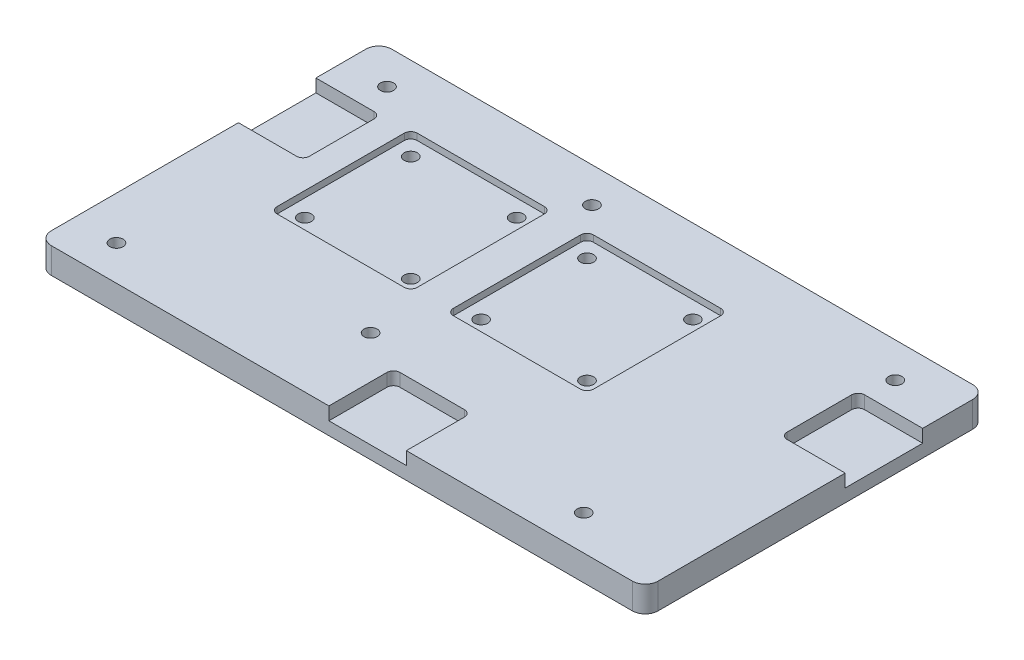
SolidWorks part; units mm, degrees
ref_plane "前视基准面" through (0, 0, 0) normal (0, 0, 1) x (1, 0, 0)
ref_plane "上视基准面" through (0, 0, 0) normal (0, 1, 0) x (1, 0, 0)
ref_plane "右视基准面" through (0, 0, 0) normal (1, 0, 0) x (0, 0, -1)
sketch "草图1" plane through (0, 0, 0) normal (0, 1, 0) x (1, 0, 0)
  line L0 (110.3086, -98.0497) -> (110.6023, -98.1284)
  line L1 (110.6023, -98.1284) -> (110.8833, -98.2448)
  line L2 (110.8833, -98.2448) -> (111.1467, -98.3968)
  line L3 (111.1467, -98.3968) -> (111.388, -98.582)
  line L4 (111.388, -98.582) -> (111.603, -98.797)
  line L5 (111.603, -98.797) -> (111.7882, -99.0383)
  line L6 (111.7882, -99.0383) -> (111.9402, -99.3017)
  line L7 (111.9402, -99.3017) -> (112.0566, -99.5827)
  line L8 (112.0566, -99.5827) -> (112.1353, -99.8764)
  line L9 (112.1353, -99.8764) -> (112.175, -100.1779)
  line L10 (112.175, -100.1779) -> (112.175, -100.4821)
  line L11 (112.175, -100.4821) -> (112.1353, -100.7836)
  line L12 (112.1353, -100.7836) -> (112.0566, -101.0773)
  line L13 (112.0566, -101.0773) -> (111.9402, -101.3583)
  line L14 (111.9402, -101.3583) -> (111.7882, -101.6217)
  line L15 (111.7882, -101.6217) -> (111.603, -101.863)
  line L16 (111.603, -101.863) -> (111.388, -102.078)
  line L17 (111.388, -102.078) -> (111.1467, -102.2632)
  line L18 (111.1467, -102.2632) -> (110.8833, -102.4152)
  line L19 (110.8833, -102.4152) -> (110.6023, -102.5316)
  line L20 (110.6023, -102.5316) -> (110.3086, -102.6103)
  line L21 (110.3086, -102.6103) -> (110.0071, -102.65)
  line L22 (110.0071, -102.65) -> (109.7029, -102.65)
  line L23 (109.7029, -102.65) -> (109.4014, -102.6103)
  line L24 (109.4014, -102.6103) -> (109.1077, -102.5316)
  line L25 (109.1077, -102.5316) -> (108.8267, -102.4152)
  line L26 (108.8267, -102.4152) -> (108.5633, -102.2632)
  line L27 (108.5633, -102.2632) -> (108.322, -102.078)
  line L28 (108.322, -102.078) -> (108.107, -101.863)
  line L29 (108.107, -101.863) -> (107.9218, -101.6217)
  line L30 (107.9218, -101.6217) -> (107.7698, -101.3583)
  line L31 (107.7698, -101.3583) -> (107.6534, -101.0773)
  line L32 (107.6534, -101.0773) -> (107.5747, -100.7836)
  line L33 (107.5747, -100.7836) -> (107.535, -100.4821)
  line L34 (107.535, -100.4821) -> (107.535, -100.1874)
  line L35 (107.535, -100.1874) -> (107.535, -100.1779)
  line L36 (107.535, -100.1779) -> (107.5747, -99.8764)
  line L37 (107.5747, -99.8764) -> (107.6534, -99.5827)
  line L38 (107.6534, -99.5827) -> (107.7698, -99.3017)
  line L39 (107.7698, -99.3017) -> (107.9218, -99.0383)
  line L40 (107.9218, -99.0383) -> (108.107, -98.797)
  line L41 (108.107, -98.797) -> (108.322, -98.582)
  line L42 (108.322, -98.582) -> (108.5633, -98.3968)
  line L43 (108.5633, -98.3968) -> (108.8267, -98.2448)
  line L44 (108.8267, -98.2448) -> (109.1077, -98.1284)
  line L45 (109.1077, -98.1284) -> (109.4014, -98.0497)
  line L46 (109.4014, -98.0497) -> (109.7029, -98.01)
  line L47 (109.7029, -98.01) -> (110.0071, -98.01)
  line L48 (110.0071, -98.01) -> (110.3086, -98.0497)
  line L49 (107.68, -100.4726) -> (107.7172, -100.7552)
  line L50 (107.7172, -100.7552) -> (107.791, -101.0306)
  line L51 (107.791, -101.0306) -> (107.9001, -101.294)
  line L52 (107.9001, -101.294) -> (108.0427, -101.541)
  line L53 (108.0427, -101.541) -> (108.2162, -101.7672)
  line L54 (108.2162, -101.7672) -> (108.4178, -101.9688)
  line L55 (108.4178, -101.9688) -> (108.644, -102.1423)
  line L56 (108.644, -102.1423) -> (108.891, -102.2849)
  line L57 (108.891, -102.2849) -> (109.1544, -102.394)
  line L58 (109.1544, -102.394) -> (109.4298, -102.4678)
  line L59 (109.4298, -102.4678) -> (109.7124, -102.505)
  line L60 (109.7124, -102.505) -> (109.9976, -102.505)
  line L61 (109.9976, -102.505) -> (110.2802, -102.4678)
  line L62 (110.2802, -102.4678) -> (110.5556, -102.394)
  line L63 (110.5556, -102.394) -> (110.819, -102.2849)
  line L64 (110.819, -102.2849) -> (111.066, -102.1423)
  line L65 (111.066, -102.1423) -> (111.2922, -101.9688)
  line L66 (111.2922, -101.9688) -> (111.4938, -101.7672)
  line L67 (111.4938, -101.7672) -> (111.6673, -101.541)
  line L68 (111.6673, -101.541) -> (111.8099, -101.294)
  line L69 (111.8099, -101.294) -> (111.919, -101.0306)
  line L70 (111.919, -101.0306) -> (111.9928, -100.7552)
  line L71 (111.9928, -100.7552) -> (112.03, -100.4726)
  line L72 (112.03, -100.4726) -> (112.03, -100.1874)
  line L73 (112.03, -100.1874) -> (111.9928, -99.9048)
  line L74 (111.9928, -99.9048) -> (111.919, -99.6294)
  line L75 (111.919, -99.6294) -> (111.8099, -99.366)
  line L76 (111.8099, -99.366) -> (111.6673, -99.119)
  line L77 (111.6673, -99.119) -> (111.4938, -98.8928)
  line L78 (111.4938, -98.8928) -> (111.2922, -98.6912)
  line L79 (111.2922, -98.6912) -> (111.066, -98.5177)
  line L80 (111.066, -98.5177) -> (110.819, -98.3751)
  line L81 (110.819, -98.3751) -> (110.5556, -98.266)
  line L82 (110.5556, -98.266) -> (110.2802, -98.1922)
  line L83 (110.2802, -98.1922) -> (109.9976, -98.155)
  line L84 (109.9976, -98.155) -> (109.7124, -98.155)
  line L85 (109.7124, -98.155) -> (109.4298, -98.1922)
  line L86 (109.4298, -98.1922) -> (109.1544, -98.266)
  line L87 (109.1544, -98.266) -> (108.891, -98.3751)
  line L88 (108.891, -98.3751) -> (108.644, -98.5177)
  line L89 (108.644, -98.5177) -> (108.4178, -98.6912)
  line L90 (108.4178, -98.6912) -> (108.2162, -98.8928)
  line L91 (108.2162, -98.8928) -> (108.0427, -99.119)
  line L92 (108.0427, -99.119) -> (107.9001, -99.366)
  line L93 (107.9001, -99.366) -> (107.791, -99.6294)
  line L94 (107.791, -99.6294) -> (107.7172, -99.9048)
  line L95 (107.7172, -99.9048) -> (107.68, -100.1874)
  line L96 (107.68, -100.1874) -> (107.68, -100.4726)
  line L97 (182.6986, -98.0497) -> (182.9923, -98.1284)
  line L98 (182.9923, -98.1284) -> (183.2733, -98.2448)
  line L99 (183.2733, -98.2448) -> (183.5367, -98.3968)
  line L100 (183.5367, -98.3968) -> (183.778, -98.582)
  line L101 (183.778, -98.582) -> (183.993, -98.797)
  line L102 (183.993, -98.797) -> (184.1782, -99.0383)
  line L103 (184.1782, -99.0383) -> (184.3302, -99.3017)
  line L104 (184.3302, -99.3017) -> (184.4466, -99.5827)
  line L105 (184.4466, -99.5827) -> (184.5253, -99.8764)
  line L106 (184.5253, -99.8764) -> (184.565, -100.1779)
  line L107 (184.565, -100.1779) -> (184.565, -100.4821)
  line L108 (184.565, -100.4821) -> (184.5253, -100.7836)
  line L109 (184.5253, -100.7836) -> (184.4466, -101.0773)
  line L110 (184.4466, -101.0773) -> (184.3302, -101.3583)
  line L111 (184.3302, -101.3583) -> (184.1782, -101.6217)
  line L112 (184.1782, -101.6217) -> (183.993, -101.863)
  line L113 (183.993, -101.863) -> (183.778, -102.078)
  line L114 (183.778, -102.078) -> (183.5367, -102.2632)
  line L115 (183.5367, -102.2632) -> (183.2733, -102.4152)
  line L116 (183.2733, -102.4152) -> (182.9923, -102.5316)
  line L117 (182.9923, -102.5316) -> (182.6986, -102.6103)
  line L118 (182.6986, -102.6103) -> (182.3971, -102.65)
  line L119 (182.3971, -102.65) -> (182.0929, -102.65)
  line L120 (182.0929, -102.65) -> (181.7914, -102.6103)
  line L121 (181.7914, -102.6103) -> (181.4977, -102.5316)
  line L122 (181.4977, -102.5316) -> (181.2167, -102.4152)
  line L123 (181.2167, -102.4152) -> (180.9533, -102.2632)
  line L124 (180.9533, -102.2632) -> (180.712, -102.078)
  line L125 (180.712, -102.078) -> (180.497, -101.863)
  line L126 (180.497, -101.863) -> (180.3118, -101.6217)
  line L127 (180.3118, -101.6217) -> (180.1598, -101.3583)
  line L128 (180.1598, -101.3583) -> (180.0434, -101.0773)
  line L129 (180.0434, -101.0773) -> (179.9647, -100.7836)
  line L130 (179.9647, -100.7836) -> (179.925, -100.4821)
  line L131 (179.925, -100.4821) -> (179.925, -100.1874)
  line L132 (179.925, -100.1874) -> (179.925, -100.1779)
  line L133 (179.925, -100.1779) -> (179.9647, -99.8764)
  line L134 (179.9647, -99.8764) -> (180.0434, -99.5827)
  line L135 (180.0434, -99.5827) -> (180.1598, -99.3017)
  line L136 (180.1598, -99.3017) -> (180.3118, -99.0383)
  line L137 (180.3118, -99.0383) -> (180.497, -98.797)
  line L138 (180.497, -98.797) -> (180.712, -98.582)
  line L139 (180.712, -98.582) -> (180.9533, -98.3968)
  line L140 (180.9533, -98.3968) -> (181.2167, -98.2448)
  line L141 (181.2167, -98.2448) -> (181.4977, -98.1284)
  line L142 (181.4977, -98.1284) -> (181.7914, -98.0497)
  line L143 (181.7914, -98.0497) -> (182.0929, -98.01)
  line L144 (182.0929, -98.01) -> (182.3971, -98.01)
  line L145 (182.3971, -98.01) -> (182.6986, -98.0497)
  line L146 (180.07, -100.4726) -> (180.1072, -100.7552)
  line L147 (180.1072, -100.7552) -> (180.181, -101.0306)
  line L148 (180.181, -101.0306) -> (180.2901, -101.294)
  line L149 (180.2901, -101.294) -> (180.4327, -101.541)
  line L150 (180.4327, -101.541) -> (180.6062, -101.7672)
  line L151 (180.6062, -101.7672) -> (180.8078, -101.9688)
  line L152 (180.8078, -101.9688) -> (181.034, -102.1423)
  line L153 (181.034, -102.1423) -> (181.281, -102.2849)
  line L154 (181.281, -102.2849) -> (181.5444, -102.394)
  line L155 (181.5444, -102.394) -> (181.8198, -102.4678)
  line L156 (181.8198, -102.4678) -> (182.1024, -102.505)
  line L157 (182.1024, -102.505) -> (182.3876, -102.505)
  line L158 (182.3876, -102.505) -> (182.6702, -102.4678)
  line L159 (182.6702, -102.4678) -> (182.9456, -102.394)
  line L160 (182.9456, -102.394) -> (183.209, -102.2849)
  line L161 (183.209, -102.2849) -> (183.456, -102.1423)
  line L162 (183.456, -102.1423) -> (183.6822, -101.9688)
  line L163 (183.6822, -101.9688) -> (183.8838, -101.7672)
  line L164 (183.8838, -101.7672) -> (184.0573, -101.541)
  line L165 (184.0573, -101.541) -> (184.1999, -101.294)
  line L166 (184.1999, -101.294) -> (184.309, -101.0306)
  line L167 (184.309, -101.0306) -> (184.3828, -100.7552)
  line L168 (184.3828, -100.7552) -> (184.42, -100.4726)
  line L169 (184.42, -100.4726) -> (184.42, -100.1874)
  line L170 (184.42, -100.1874) -> (184.3828, -99.9048)
  line L171 (184.3828, -99.9048) -> (184.309, -99.6294)
  line L172 (184.309, -99.6294) -> (184.1999, -99.366)
  line L173 (184.1999, -99.366) -> (184.0573, -99.119)
  line L174 (184.0573, -99.119) -> (183.8838, -98.8928)
  line L175 (183.8838, -98.8928) -> (183.6822, -98.6912)
  line L176 (183.6822, -98.6912) -> (183.456, -98.5177)
  line L177 (183.456, -98.5177) -> (183.209, -98.3751)
  line L178 (183.209, -98.3751) -> (182.9456, -98.266)
  line L179 (182.9456, -98.266) -> (182.6702, -98.1922)
  line L180 (182.6702, -98.1922) -> (182.3876, -98.155)
  line L181 (182.3876, -98.155) -> (182.1024, -98.155)
  line L182 (182.1024, -98.155) -> (181.8198, -98.1922)
  line L183 (181.8198, -98.1922) -> (181.5444, -98.266)
  line L184 (181.5444, -98.266) -> (181.281, -98.3751)
  line L185 (181.281, -98.3751) -> (181.034, -98.5177)
  line L186 (181.034, -98.5177) -> (180.8078, -98.6912)
  line L187 (180.8078, -98.6912) -> (180.6062, -98.8928)
  line L188 (180.6062, -98.8928) -> (180.4327, -99.119)
  line L189 (180.4327, -99.119) -> (180.2901, -99.366)
  line L190 (180.2901, -99.366) -> (180.181, -99.6294)
  line L191 (180.181, -99.6294) -> (180.1072, -99.9048)
  line L192 (180.1072, -99.9048) -> (180.07, -100.1874)
  line L193 (180.07, -100.1874) -> (180.07, -100.4726)
  line L194 (142.0586, -90.4297) -> (142.3523, -90.5084)
  line L195 (142.3523, -90.5084) -> (142.6333, -90.6248)
  line L196 (142.6333, -90.6248) -> (142.8967, -90.7768)
  line L197 (142.8967, -90.7768) -> (143.138, -90.962)
  line L198 (143.138, -90.962) -> (143.353, -91.177)
  line L199 (143.353, -91.177) -> (143.5382, -91.4183)
  line L200 (143.5382, -91.4183) -> (143.6902, -91.6817)
  line L201 (143.6902, -91.6817) -> (143.8066, -91.9627)
  line L202 (143.8066, -91.9627) -> (143.8853, -92.2564)
  line L203 (143.8853, -92.2564) -> (143.925, -92.5579)
  line L204 (143.925, -92.5579) -> (143.925, -92.8621)
  line L205 (143.925, -92.8621) -> (143.8853, -93.1636)
  line L206 (143.8853, -93.1636) -> (143.8066, -93.4573)
  line L207 (143.8066, -93.4573) -> (143.6902, -93.7383)
  line L208 (143.6902, -93.7383) -> (143.5382, -94.0017)
  line L209 (143.5382, -94.0017) -> (143.353, -94.243)
  line L210 (143.353, -94.243) -> (143.138, -94.458)
  line L211 (143.138, -94.458) -> (142.8967, -94.6432)
  line L212 (142.8967, -94.6432) -> (142.6333, -94.7952)
  line L213 (142.6333, -94.7952) -> (142.3523, -94.9116)
  line L214 (142.3523, -94.9116) -> (142.0586, -94.9903)
  line L215 (142.0586, -94.9903) -> (141.7571, -95.03)
  line L216 (141.7571, -95.03) -> (141.4529, -95.03)
  line L217 (141.4529, -95.03) -> (141.1514, -94.9903)
  line L218 (141.1514, -94.9903) -> (140.8577, -94.9116)
  line L219 (140.8577, -94.9116) -> (140.5767, -94.7952)
  line L220 (140.5767, -94.7952) -> (140.3133, -94.6432)
  line L221 (140.3133, -94.6432) -> (140.072, -94.458)
  line L222 (140.072, -94.458) -> (139.857, -94.243)
  line L223 (139.857, -94.243) -> (139.6718, -94.0017)
  line L224 (139.6718, -94.0017) -> (139.5198, -93.7383)
  line L225 (139.5198, -93.7383) -> (139.4034, -93.4573)
  line L226 (139.4034, -93.4573) -> (139.3247, -93.1636)
  line L227 (139.3247, -93.1636) -> (139.285, -92.8621)
  line L228 (139.285, -92.8621) -> (139.285, -92.5674)
  line L229 (139.285, -92.5674) -> (139.285, -92.5579)
  line L230 (139.285, -92.5579) -> (139.3247, -92.2564)
  line L231 (139.3247, -92.2564) -> (139.4034, -91.9627)
  line L232 (139.4034, -91.9627) -> (139.5198, -91.6817)
  line L233 (139.5198, -91.6817) -> (139.6718, -91.4183)
  line L234 (139.6718, -91.4183) -> (139.857, -91.177)
  line L235 (139.857, -91.177) -> (140.072, -90.962)
  line L236 (140.072, -90.962) -> (140.3133, -90.7768)
  line L237 (140.3133, -90.7768) -> (140.5767, -90.6248)
  line L238 (140.5767, -90.6248) -> (140.8577, -90.5084)
  line L239 (140.8577, -90.5084) -> (141.1514, -90.4297)
  line L240 (141.1514, -90.4297) -> (141.4529, -90.39)
  line L241 (141.4529, -90.39) -> (141.7571, -90.39)
  line L242 (141.7571, -90.39) -> (142.0586, -90.4297)
  line L243 (139.43, -92.8526) -> (139.4672, -93.1352)
  line L244 (139.4672, -93.1352) -> (139.541, -93.4106)
  line L245 (139.541, -93.4106) -> (139.6501, -93.674)
  line L246 (139.6501, -93.674) -> (139.7927, -93.921)
  line L247 (139.7927, -93.921) -> (139.9662, -94.1472)
  line L248 (139.9662, -94.1472) -> (140.1678, -94.3488)
  line L249 (140.1678, -94.3488) -> (140.394, -94.5223)
  line L250 (140.394, -94.5223) -> (140.641, -94.6649)
  line L251 (140.641, -94.6649) -> (140.9044, -94.774)
  line L252 (140.9044, -94.774) -> (141.1798, -94.8478)
  line L253 (141.1798, -94.8478) -> (141.4624, -94.885)
  line L254 (141.4624, -94.885) -> (141.7476, -94.885)
  line L255 (141.7476, -94.885) -> (142.0302, -94.8478)
  line L256 (142.0302, -94.8478) -> (142.3056, -94.774)
  line L257 (142.3056, -94.774) -> (142.569, -94.6649)
  line L258 (142.569, -94.6649) -> (142.816, -94.5223)
  line L259 (142.816, -94.5223) -> (143.0422, -94.3488)
  line L260 (143.0422, -94.3488) -> (143.2438, -94.1472)
  line L261 (143.2438, -94.1472) -> (143.4173, -93.921)
  line L262 (143.4173, -93.921) -> (143.5599, -93.674)
  line L263 (143.5599, -93.674) -> (143.669, -93.4106)
  line L264 (143.669, -93.4106) -> (143.7428, -93.1352)
  line L265 (143.7428, -93.1352) -> (143.78, -92.8526)
  line L266 (143.78, -92.8526) -> (143.78, -92.5674)
  line L267 (143.78, -92.5674) -> (143.7428, -92.2848)
  line L268 (143.7428, -92.2848) -> (143.669, -92.0094)
  line L269 (143.669, -92.0094) -> (143.5599, -91.746)
  line L270 (143.5599, -91.746) -> (143.4173, -91.499)
  line L271 (143.4173, -91.499) -> (143.2438, -91.2728)
  line L272 (143.2438, -91.2728) -> (143.0422, -91.0712)
  line L273 (143.0422, -91.0712) -> (142.816, -90.8977)
  line L274 (142.816, -90.8977) -> (142.569, -90.7551)
  line L275 (142.569, -90.7551) -> (142.3056, -90.646)
  line L276 (142.3056, -90.646) -> (142.0302, -90.5722)
  line L277 (142.0302, -90.5722) -> (141.7476, -90.535)
  line L278 (141.7476, -90.535) -> (141.4624, -90.535)
  line L279 (141.4624, -90.535) -> (141.1798, -90.5722)
  line L280 (141.1798, -90.5722) -> (140.9044, -90.646)
  line L281 (140.9044, -90.646) -> (140.641, -90.7551)
  line L282 (140.641, -90.7551) -> (140.394, -90.8977)
  line L283 (140.394, -90.8977) -> (140.1678, -91.0712)
  line L284 (140.1678, -91.0712) -> (139.9662, -91.2728)
  line L285 (139.9662, -91.2728) -> (139.7927, -91.499)
  line L286 (139.7927, -91.499) -> (139.6501, -91.746)
  line L287 (139.6501, -91.746) -> (139.541, -92.0094)
  line L288 (139.541, -92.0094) -> (139.4672, -92.2848)
  line L289 (139.4672, -92.2848) -> (139.43, -92.5674)
  line L290 (139.43, -92.5674) -> (139.43, -92.8526)
  line L291 (120.3735, -80.0879) -> (120.5675, -80.151)
  line L292 (120.5675, -80.151) -> (120.7492, -80.2436)
  line L293 (120.7492, -80.2436) -> (120.9143, -80.3635)
  line L294 (120.9143, -80.3635) -> (121.0585, -80.5077)
  line L295 (121.0585, -80.5077) -> (121.1784, -80.6728)
  line L296 (121.1784, -80.6728) -> (121.271, -80.8545)
  line L297 (121.271, -80.8545) -> (121.3341, -81.0485)
  line L298 (121.3341, -81.0485) -> (121.366, -81.25)
  line L299 (121.366, -81.25) -> (121.366, -81.454)
  line L300 (121.366, -81.454) -> (121.3341, -81.6555)
  line L301 (121.3341, -81.6555) -> (121.271, -81.8495)
  line L302 (121.271, -81.8495) -> (121.1784, -82.0312)
  line L303 (121.1784, -82.0312) -> (121.0585, -82.1963)
  line L304 (121.0585, -82.1963) -> (120.9143, -82.3405)
  line L305 (120.9143, -82.3405) -> (120.7492, -82.4604)
  line L306 (120.7492, -82.4604) -> (120.5675, -82.553)
  line L307 (120.5675, -82.553) -> (120.3735, -82.6161)
  line L308 (120.3735, -82.6161) -> (120.172, -82.648)
  line L309 (120.172, -82.648) -> (119.968, -82.648)
  line L310 (119.968, -82.648) -> (119.7665, -82.6161)
  line L311 (119.7665, -82.6161) -> (119.5725, -82.553)
  line L312 (119.5725, -82.553) -> (119.3908, -82.4604)
  line L313 (119.3908, -82.4604) -> (119.2257, -82.3405)
  line L314 (119.2257, -82.3405) -> (119.0815, -82.1963)
  line L315 (119.0815, -82.1963) -> (118.9616, -82.0312)
  line L316 (118.9616, -82.0312) -> (118.869, -81.8495)
  line L317 (118.869, -81.8495) -> (118.8059, -81.6555)
  line L318 (118.8059, -81.6555) -> (118.774, -81.454)
  line L319 (118.774, -81.454) -> (118.774, -81.2576)
  line L320 (118.774, -81.2576) -> (118.774, -81.25)
  line L321 (118.774, -81.25) -> (118.8059, -81.0485)
  line L322 (118.8059, -81.0485) -> (118.869, -80.8545)
  line L323 (118.869, -80.8545) -> (118.9616, -80.6728)
  line L324 (118.9616, -80.6728) -> (119.0815, -80.5077)
  line L325 (119.0815, -80.5077) -> (119.2257, -80.3635)
  line L326 (119.2257, -80.3635) -> (119.3908, -80.2436)
  line L327 (119.3908, -80.2436) -> (119.5725, -80.151)
  line L328 (119.5725, -80.151) -> (119.7665, -80.0879)
  line L329 (119.7665, -80.0879) -> (119.968, -80.056)
  line L330 (119.968, -80.056) -> (120.172, -80.056)
  line L331 (120.172, -80.056) -> (120.3735, -80.0879)
  line L332 (118.87, -81.4464) -> (118.8995, -81.633)
  line L333 (118.8995, -81.633) -> (118.9579, -81.8126)
  line L334 (118.9579, -81.8126) -> (119.0437, -81.9809)
  line L335 (119.0437, -81.9809) -> (119.1547, -82.1337)
  line L336 (119.1547, -82.1337) -> (119.2883, -82.2673)
  line L337 (119.2883, -82.2673) -> (119.4411, -82.3783)
  line L338 (119.4411, -82.3783) -> (119.6094, -82.4641)
  line L339 (119.6094, -82.4641) -> (119.789, -82.5225)
  line L340 (119.789, -82.5225) -> (119.9756, -82.552)
  line L341 (119.9756, -82.552) -> (120.1644, -82.552)
  line L342 (120.1644, -82.552) -> (120.351, -82.5225)
  line L343 (120.351, -82.5225) -> (120.5306, -82.4641)
  line L344 (120.5306, -82.4641) -> (120.6989, -82.3783)
  line L345 (120.6989, -82.3783) -> (120.8517, -82.2673)
  line L346 (120.8517, -82.2673) -> (120.9853, -82.1337)
  line L347 (120.9853, -82.1337) -> (121.0963, -81.9809)
  line L348 (121.0963, -81.9809) -> (121.1821, -81.8126)
  line L349 (121.1821, -81.8126) -> (121.2405, -81.633)
  line L350 (121.2405, -81.633) -> (121.27, -81.4464)
  line L351 (121.27, -81.4464) -> (121.27, -81.2576)
  line L352 (121.27, -81.2576) -> (121.2405, -81.071)
  line L353 (121.2405, -81.071) -> (121.1821, -80.8914)
  line L354 (121.1821, -80.8914) -> (121.0963, -80.7231)
  line L355 (121.0963, -80.7231) -> (120.9853, -80.5703)
  line L356 (120.9853, -80.5703) -> (120.8517, -80.4367)
  line L357 (120.8517, -80.4367) -> (120.6989, -80.3257)
  line L358 (120.6989, -80.3257) -> (120.5306, -80.2399)
  line L359 (120.5306, -80.2399) -> (120.351, -80.1815)
  line L360 (120.351, -80.1815) -> (120.1644, -80.152)
  line L361 (120.1644, -80.152) -> (119.9756, -80.152)
  line L362 (119.9756, -80.152) -> (119.789, -80.1815)
  line L363 (119.789, -80.1815) -> (119.6094, -80.2399)
  line L364 (119.6094, -80.2399) -> (119.4411, -80.3257)
  line L365 (119.4411, -80.3257) -> (119.2883, -80.4367)
  line L366 (119.2883, -80.4367) -> (119.1547, -80.5703)
  line L367 (119.1547, -80.5703) -> (119.0437, -80.7231)
  line L368 (119.0437, -80.7231) -> (118.9579, -80.8914)
  line L369 (118.9579, -80.8914) -> (118.8995, -81.071)
  line L370 (118.8995, -81.071) -> (118.87, -81.2576)
  line L371 (118.87, -81.2576) -> (118.87, -81.4464)
  line L372 (136.7735, -80.0879) -> (136.9675, -80.151)
  line L373 (136.9675, -80.151) -> (137.1492, -80.2436)
  line L374 (137.1492, -80.2436) -> (137.3143, -80.3635)
  line L375 (137.3143, -80.3635) -> (137.4585, -80.5077)
  line L376 (137.4585, -80.5077) -> (137.5784, -80.6728)
  line L377 (137.5784, -80.6728) -> (137.671, -80.8545)
  line L378 (137.671, -80.8545) -> (137.7341, -81.0485)
  line L379 (137.7341, -81.0485) -> (137.766, -81.25)
  line L380 (137.766, -81.25) -> (137.766, -81.454)
  line L381 (137.766, -81.454) -> (137.7341, -81.6555)
  line L382 (137.7341, -81.6555) -> (137.671, -81.8495)
  line L383 (137.671, -81.8495) -> (137.5784, -82.0312)
  line L384 (137.5784, -82.0312) -> (137.4585, -82.1963)
  line L385 (137.4585, -82.1963) -> (137.3143, -82.3405)
  line L386 (137.3143, -82.3405) -> (137.1492, -82.4604)
  line L387 (137.1492, -82.4604) -> (136.9675, -82.553)
  line L388 (136.9675, -82.553) -> (136.7735, -82.6161)
  line L389 (136.7735, -82.6161) -> (136.572, -82.648)
  line L390 (136.572, -82.648) -> (136.368, -82.648)
  line L391 (136.368, -82.648) -> (136.1665, -82.6161)
  line L392 (136.1665, -82.6161) -> (135.9725, -82.553)
  line L393 (135.9725, -82.553) -> (135.7908, -82.4604)
  line L394 (135.7908, -82.4604) -> (135.6257, -82.3405)
  line L395 (135.6257, -82.3405) -> (135.4815, -82.1963)
  line L396 (135.4815, -82.1963) -> (135.3616, -82.0312)
  line L397 (135.3616, -82.0312) -> (135.269, -81.8495)
  line L398 (135.269, -81.8495) -> (135.2059, -81.6555)
  line L399 (135.2059, -81.6555) -> (135.174, -81.454)
  line L400 (135.174, -81.454) -> (135.174, -81.2576)
  line L401 (135.174, -81.2576) -> (135.174, -81.25)
  line L402 (135.174, -81.25) -> (135.2059, -81.0485)
  line L403 (135.2059, -81.0485) -> (135.269, -80.8545)
  line L404 (135.269, -80.8545) -> (135.3616, -80.6728)
  line L405 (135.3616, -80.6728) -> (135.4815, -80.5077)
  line L406 (135.4815, -80.5077) -> (135.6257, -80.3635)
  line L407 (135.6257, -80.3635) -> (135.7908, -80.2436)
  line L408 (135.7908, -80.2436) -> (135.9725, -80.151)
  line L409 (135.9725, -80.151) -> (136.1665, -80.0879)
  line L410 (136.1665, -80.0879) -> (136.368, -80.056)
  line L411 (136.368, -80.056) -> (136.572, -80.056)
  line L412 (136.572, -80.056) -> (136.7735, -80.0879)
  line L413 (135.27, -81.4464) -> (135.2995, -81.633)
  line L414 (135.2995, -81.633) -> (135.3579, -81.8126)
  line L415 (135.3579, -81.8126) -> (135.4437, -81.9809)
  line L416 (135.4437, -81.9809) -> (135.5547, -82.1337)
  line L417 (135.5547, -82.1337) -> (135.6883, -82.2673)
  line L418 (135.6883, -82.2673) -> (135.8411, -82.3783)
  line L419 (135.8411, -82.3783) -> (136.0094, -82.4641)
  line L420 (136.0094, -82.4641) -> (136.189, -82.5225)
  line L421 (136.189, -82.5225) -> (136.3756, -82.552)
  line L422 (136.3756, -82.552) -> (136.5644, -82.552)
  line L423 (136.5644, -82.552) -> (136.751, -82.5225)
  line L424 (136.751, -82.5225) -> (136.9306, -82.4641)
  line L425 (136.9306, -82.4641) -> (137.0989, -82.3783)
  line L426 (137.0989, -82.3783) -> (137.2517, -82.2673)
  line L427 (137.2517, -82.2673) -> (137.3853, -82.1337)
  line L428 (137.3853, -82.1337) -> (137.4963, -81.9809)
  line L429 (137.4963, -81.9809) -> (137.5821, -81.8126)
  line L430 (137.5821, -81.8126) -> (137.6405, -81.633)
  line L431 (137.6405, -81.633) -> (137.67, -81.4464)
  line L432 (137.67, -81.4464) -> (137.67, -81.2576)
  line L433 (137.67, -81.2576) -> (137.6405, -81.071)
  line L434 (137.6405, -81.071) -> (137.5821, -80.8914)
  line L435 (137.5821, -80.8914) -> (137.4963, -80.7231)
  line L436 (137.4963, -80.7231) -> (137.3853, -80.5703)
  line L437 (137.3853, -80.5703) -> (137.2517, -80.4367)
  line L438 (137.2517, -80.4367) -> (137.0989, -80.3257)
  line L439 (137.0989, -80.3257) -> (136.9306, -80.2399)
  line L440 (136.9306, -80.2399) -> (136.751, -80.1815)
  line L441 (136.751, -80.1815) -> (136.5644, -80.152)
  line L442 (136.5644, -80.152) -> (136.3756, -80.152)
  line L443 (136.3756, -80.152) -> (136.189, -80.1815)
  line L444 (136.189, -80.1815) -> (136.0094, -80.2399)
  line L445 (136.0094, -80.2399) -> (135.8411, -80.3257)
  line L446 (135.8411, -80.3257) -> (135.6883, -80.4367)
  line L447 (135.6883, -80.4367) -> (135.5547, -80.5703)
  line L448 (135.5547, -80.5703) -> (135.4437, -80.7231)
  line L449 (135.4437, -80.7231) -> (135.3579, -80.8914)
  line L450 (135.3579, -80.8914) -> (135.2995, -81.071)
  line L451 (135.2995, -81.071) -> (135.27, -81.2576)
  line L452 (135.27, -81.2576) -> (135.27, -81.4464)
  line L453 (147.6785, -80.0879) -> (147.8725, -80.151)
  line L454 (147.8725, -80.151) -> (148.0542, -80.2436)
  line L455 (148.0542, -80.2436) -> (148.2193, -80.3635)
  line L456 (148.2193, -80.3635) -> (148.3635, -80.5077)
  line L457 (148.3635, -80.5077) -> (148.4834, -80.6728)
  line L458 (148.4834, -80.6728) -> (148.576, -80.8545)
  line L459 (148.576, -80.8545) -> (148.6391, -81.0485)
  line L460 (148.6391, -81.0485) -> (148.671, -81.25)
  line L461 (148.671, -81.25) -> (148.671, -81.454)
  line L462 (148.671, -81.454) -> (148.6391, -81.6555)
  line L463 (148.6391, -81.6555) -> (148.576, -81.8495)
  line L464 (148.576, -81.8495) -> (148.4834, -82.0312)
  line L465 (148.4834, -82.0312) -> (148.3635, -82.1963)
  line L466 (148.3635, -82.1963) -> (148.2193, -82.3405)
  line L467 (148.2193, -82.3405) -> (148.0542, -82.4604)
  line L468 (148.0542, -82.4604) -> (147.8725, -82.553)
  line L469 (147.8725, -82.553) -> (147.6785, -82.6161)
  line L470 (147.6785, -82.6161) -> (147.477, -82.648)
  line L471 (147.477, -82.648) -> (147.273, -82.648)
  line L472 (147.273, -82.648) -> (147.0715, -82.6161)
  line L473 (147.0715, -82.6161) -> (146.8775, -82.553)
  line L474 (146.8775, -82.553) -> (146.6958, -82.4604)
  line L475 (146.6958, -82.4604) -> (146.5307, -82.3405)
  line L476 (146.5307, -82.3405) -> (146.3865, -82.1963)
  line L477 (146.3865, -82.1963) -> (146.2666, -82.0312)
  line L478 (146.2666, -82.0312) -> (146.174, -81.8495)
  line L479 (146.174, -81.8495) -> (146.1109, -81.6555)
  line L480 (146.1109, -81.6555) -> (146.079, -81.454)
  line L481 (146.079, -81.454) -> (146.079, -81.2576)
  line L482 (146.079, -81.2576) -> (146.079, -81.25)
  line L483 (146.079, -81.25) -> (146.1109, -81.0485)
  line L484 (146.1109, -81.0485) -> (146.174, -80.8545)
  line L485 (146.174, -80.8545) -> (146.2666, -80.6728)
  line L486 (146.2666, -80.6728) -> (146.3865, -80.5077)
  line L487 (146.3865, -80.5077) -> (146.5307, -80.3635)
  line L488 (146.5307, -80.3635) -> (146.6958, -80.2436)
  line L489 (146.6958, -80.2436) -> (146.8775, -80.151)
  line L490 (146.8775, -80.151) -> (147.0715, -80.0879)
  line L491 (147.0715, -80.0879) -> (147.273, -80.056)
  line L492 (147.273, -80.056) -> (147.477, -80.056)
  line L493 (147.477, -80.056) -> (147.6785, -80.0879)
  line L494 (146.175, -81.4464) -> (146.2045, -81.633)
  line L495 (146.2045, -81.633) -> (146.2629, -81.8126)
  line L496 (146.2629, -81.8126) -> (146.3487, -81.9809)
  line L497 (146.3487, -81.9809) -> (146.4597, -82.1337)
  line L498 (146.4597, -82.1337) -> (146.5933, -82.2673)
  line L499 (146.5933, -82.2673) -> (146.7461, -82.3783)
  line L500 (146.7461, -82.3783) -> (146.9144, -82.4641)
  line L501 (146.9144, -82.4641) -> (147.094, -82.5225)
  line L502 (147.094, -82.5225) -> (147.2806, -82.552)
  line L503 (147.2806, -82.552) -> (147.4694, -82.552)
  line L504 (147.4694, -82.552) -> (147.656, -82.5225)
  line L505 (147.656, -82.5225) -> (147.8356, -82.4641)
  line L506 (147.8356, -82.4641) -> (148.0039, -82.3783)
  line L507 (148.0039, -82.3783) -> (148.1567, -82.2673)
  line L508 (148.1567, -82.2673) -> (148.2903, -82.1337)
  line L509 (148.2903, -82.1337) -> (148.4013, -81.9809)
  line L510 (148.4013, -81.9809) -> (148.4871, -81.8126)
  line L511 (148.4871, -81.8126) -> (148.5455, -81.633)
  line L512 (148.5455, -81.633) -> (148.575, -81.4464)
  line L513 (148.575, -81.4464) -> (148.575, -81.2576)
  line L514 (148.575, -81.2576) -> (148.5455, -81.071)
  line L515 (148.5455, -81.071) -> (148.4871, -80.8914)
  line L516 (148.4871, -80.8914) -> (148.4013, -80.7231)
  line L517 (148.4013, -80.7231) -> (148.2903, -80.5703)
  line L518 (148.2903, -80.5703) -> (148.1567, -80.4367)
  line L519 (148.1567, -80.4367) -> (148.0039, -80.3257)
  line L520 (148.0039, -80.3257) -> (147.8356, -80.2399)
  line L521 (147.8356, -80.2399) -> (147.656, -80.1815)
  line L522 (147.656, -80.1815) -> (147.4694, -80.152)
  line L523 (147.4694, -80.152) -> (147.2806, -80.152)
  line L524 (147.2806, -80.152) -> (147.094, -80.1815)
  line L525 (147.094, -80.1815) -> (146.9144, -80.2399)
  line L526 (146.9144, -80.2399) -> (146.7461, -80.3257)
  line L527 (146.7461, -80.3257) -> (146.5933, -80.4367)
  line L528 (146.5933, -80.4367) -> (146.4597, -80.5703)
  line L529 (146.4597, -80.5703) -> (146.3487, -80.7231)
  line L530 (146.3487, -80.7231) -> (146.2629, -80.8914)
  line L531 (146.2629, -80.8914) -> (146.2045, -81.071)
  line L532 (146.2045, -81.071) -> (146.175, -81.2576)
  line L533 (146.175, -81.2576) -> (146.175, -81.4464)
  line L534 (164.0785, -80.0879) -> (164.2725, -80.151)
  line L535 (164.2725, -80.151) -> (164.4542, -80.2436)
  line L536 (164.4542, -80.2436) -> (164.6193, -80.3635)
  line L537 (164.6193, -80.3635) -> (164.7635, -80.5077)
  line L538 (164.7635, -80.5077) -> (164.8834, -80.6728)
  line L539 (164.8834, -80.6728) -> (164.976, -80.8545)
  line L540 (164.976, -80.8545) -> (165.0391, -81.0485)
  line L541 (165.0391, -81.0485) -> (165.071, -81.25)
  line L542 (165.071, -81.25) -> (165.071, -81.454)
  line L543 (165.071, -81.454) -> (165.0391, -81.6555)
  line L544 (165.0391, -81.6555) -> (164.976, -81.8495)
  line L545 (164.976, -81.8495) -> (164.8834, -82.0312)
  line L546 (164.8834, -82.0312) -> (164.7635, -82.1963)
  line L547 (164.7635, -82.1963) -> (164.6193, -82.3405)
  line L548 (164.6193, -82.3405) -> (164.4542, -82.4604)
  line L549 (164.4542, -82.4604) -> (164.2725, -82.553)
  line L550 (164.2725, -82.553) -> (164.0785, -82.6161)
  line L551 (164.0785, -82.6161) -> (163.877, -82.648)
  line L552 (163.877, -82.648) -> (163.673, -82.648)
  line L553 (163.673, -82.648) -> (163.4715, -82.6161)
  line L554 (163.4715, -82.6161) -> (163.2775, -82.553)
  line L555 (163.2775, -82.553) -> (163.0958, -82.4604)
  line L556 (163.0958, -82.4604) -> (162.9307, -82.3405)
  line L557 (162.9307, -82.3405) -> (162.7865, -82.1963)
  line L558 (162.7865, -82.1963) -> (162.6666, -82.0312)
  line L559 (162.6666, -82.0312) -> (162.574, -81.8495)
  line L560 (162.574, -81.8495) -> (162.5109, -81.6555)
  line L561 (162.5109, -81.6555) -> (162.479, -81.454)
  line L562 (162.479, -81.454) -> (162.479, -81.2576)
  line L563 (162.479, -81.2576) -> (162.479, -81.25)
  line L564 (162.479, -81.25) -> (162.5109, -81.0485)
  line L565 (162.5109, -81.0485) -> (162.574, -80.8545)
  line L566 (162.574, -80.8545) -> (162.6666, -80.6728)
  line L567 (162.6666, -80.6728) -> (162.7865, -80.5077)
  line L568 (162.7865, -80.5077) -> (162.9307, -80.3635)
  line L569 (162.9307, -80.3635) -> (163.0958, -80.2436)
  line L570 (163.0958, -80.2436) -> (163.2775, -80.151)
  line L571 (163.2775, -80.151) -> (163.4715, -80.0879)
  line L572 (163.4715, -80.0879) -> (163.673, -80.056)
  line L573 (163.673, -80.056) -> (163.877, -80.056)
  line L574 (163.877, -80.056) -> (164.0785, -80.0879)
  line L575 (162.575, -81.4464) -> (162.6045, -81.633)
  line L576 (162.6045, -81.633) -> (162.6629, -81.8126)
  line L577 (162.6629, -81.8126) -> (162.7487, -81.9809)
  line L578 (162.7487, -81.9809) -> (162.8597, -82.1337)
  line L579 (162.8597, -82.1337) -> (162.9933, -82.2673)
  line L580 (162.9933, -82.2673) -> (163.1461, -82.3783)
  line L581 (163.1461, -82.3783) -> (163.3144, -82.4641)
  line L582 (163.3144, -82.4641) -> (163.494, -82.5225)
  line L583 (163.494, -82.5225) -> (163.6806, -82.552)
  line L584 (163.6806, -82.552) -> (163.8694, -82.552)
  line L585 (163.8694, -82.552) -> (164.056, -82.5225)
  line L586 (164.056, -82.5225) -> (164.2356, -82.4641)
  line L587 (164.2356, -82.4641) -> (164.4039, -82.3783)
  line L588 (164.4039, -82.3783) -> (164.5567, -82.2673)
  line L589 (164.5567, -82.2673) -> (164.6903, -82.1337)
  line L590 (164.6903, -82.1337) -> (164.8013, -81.9809)
  line L591 (164.8013, -81.9809) -> (164.8871, -81.8126)
  line L592 (164.8871, -81.8126) -> (164.9455, -81.633)
  line L593 (164.9455, -81.633) -> (164.975, -81.4464)
  line L594 (164.975, -81.4464) -> (164.975, -81.2576)
  line L595 (164.975, -81.2576) -> (164.9455, -81.071)
  line L596 (164.9455, -81.071) -> (164.8871, -80.8914)
  line L597 (164.8871, -80.8914) -> (164.8013, -80.7231)
  line L598 (164.8013, -80.7231) -> (164.6903, -80.5703)
  line L599 (164.6903, -80.5703) -> (164.5567, -80.4367)
  line L600 (164.5567, -80.4367) -> (164.4039, -80.3257)
  line L601 (164.4039, -80.3257) -> (164.2356, -80.2399)
  line L602 (164.2356, -80.2399) -> (164.056, -80.1815)
  line L603 (164.056, -80.1815) -> (163.8694, -80.152)
  line L604 (163.8694, -80.152) -> (163.6806, -80.152)
  line L605 (163.6806, -80.152) -> (163.494, -80.1815)
  line L606 (163.494, -80.1815) -> (163.3144, -80.2399)
  line L607 (163.3144, -80.2399) -> (163.1461, -80.3257)
  line L608 (163.1461, -80.3257) -> (162.9933, -80.4367)
  line L609 (162.9933, -80.4367) -> (162.8597, -80.5703)
  line L610 (162.8597, -80.5703) -> (162.7487, -80.7231)
  line L611 (162.7487, -80.7231) -> (162.6629, -80.8914)
  line L612 (162.6629, -80.8914) -> (162.6045, -81.071)
  line L613 (162.6045, -81.071) -> (162.575, -81.2576)
  line L614 (162.575, -81.2576) -> (162.575, -81.4464)
  line L615 (120.3735, -63.6879) -> (120.5675, -63.751)
  line L616 (120.5675, -63.751) -> (120.7492, -63.8436)
  line L617 (120.7492, -63.8436) -> (120.9143, -63.9635)
  line L618 (120.9143, -63.9635) -> (121.0585, -64.1077)
  line L619 (121.0585, -64.1077) -> (121.1784, -64.2728)
  line L620 (121.1784, -64.2728) -> (121.271, -64.4545)
  line L621 (121.271, -64.4545) -> (121.3341, -64.6485)
  line L622 (121.3341, -64.6485) -> (121.366, -64.85)
  line L623 (121.366, -64.85) -> (121.366, -65.054)
  line L624 (121.366, -65.054) -> (121.3341, -65.2555)
  line L625 (121.3341, -65.2555) -> (121.271, -65.4495)
  line L626 (121.271, -65.4495) -> (121.1784, -65.6312)
  line L627 (121.1784, -65.6312) -> (121.0585, -65.7963)
  line L628 (121.0585, -65.7963) -> (120.9143, -65.9405)
  line L629 (120.9143, -65.9405) -> (120.7492, -66.0604)
  line L630 (120.7492, -66.0604) -> (120.5675, -66.153)
  line L631 (120.5675, -66.153) -> (120.3735, -66.2161)
  line L632 (120.3735, -66.2161) -> (120.172, -66.248)
  line L633 (120.172, -66.248) -> (119.968, -66.248)
  line L634 (119.968, -66.248) -> (119.7665, -66.2161)
  line L635 (119.7665, -66.2161) -> (119.5725, -66.153)
  line L636 (119.5725, -66.153) -> (119.3908, -66.0604)
  line L637 (119.3908, -66.0604) -> (119.2257, -65.9405)
  line L638 (119.2257, -65.9405) -> (119.0815, -65.7963)
  line L639 (119.0815, -65.7963) -> (118.9616, -65.6312)
  line L640 (118.9616, -65.6312) -> (118.869, -65.4495)
  line L641 (118.869, -65.4495) -> (118.8059, -65.2555)
  line L642 (118.8059, -65.2555) -> (118.774, -65.054)
  line L643 (118.774, -65.054) -> (118.774, -64.8576)
  line L644 (118.774, -64.8576) -> (118.774, -64.85)
  line L645 (118.774, -64.85) -> (118.8059, -64.6485)
  line L646 (118.8059, -64.6485) -> (118.869, -64.4545)
  line L647 (118.869, -64.4545) -> (118.9616, -64.2728)
  line L648 (118.9616, -64.2728) -> (119.0815, -64.1077)
  line L649 (119.0815, -64.1077) -> (119.2257, -63.9635)
  line L650 (119.2257, -63.9635) -> (119.3908, -63.8436)
  line L651 (119.3908, -63.8436) -> (119.5725, -63.751)
  line L652 (119.5725, -63.751) -> (119.7665, -63.6879)
  line L653 (119.7665, -63.6879) -> (119.968, -63.656)
  line L654 (119.968, -63.656) -> (120.172, -63.656)
  line L655 (120.172, -63.656) -> (120.3735, -63.6879)
  line L656 (118.87, -65.0464) -> (118.8995, -65.233)
  line L657 (118.8995, -65.233) -> (118.9579, -65.4126)
  line L658 (118.9579, -65.4126) -> (119.0437, -65.5809)
  line L659 (119.0437, -65.5809) -> (119.1547, -65.7337)
  line L660 (119.1547, -65.7337) -> (119.2883, -65.8673)
  line L661 (119.2883, -65.8673) -> (119.4411, -65.9783)
  line L662 (119.4411, -65.9783) -> (119.6094, -66.0641)
  line L663 (119.6094, -66.0641) -> (119.789, -66.1225)
  line L664 (119.789, -66.1225) -> (119.9756, -66.152)
  line L665 (119.9756, -66.152) -> (120.1644, -66.152)
  line L666 (120.1644, -66.152) -> (120.351, -66.1225)
  line L667 (120.351, -66.1225) -> (120.5306, -66.0641)
  line L668 (120.5306, -66.0641) -> (120.6989, -65.9783)
  line L669 (120.6989, -65.9783) -> (120.8517, -65.8673)
  line L670 (120.8517, -65.8673) -> (120.9853, -65.7337)
  line L671 (120.9853, -65.7337) -> (121.0963, -65.5809)
  line L672 (121.0963, -65.5809) -> (121.1821, -65.4126)
  line L673 (121.1821, -65.4126) -> (121.2405, -65.233)
  line L674 (121.2405, -65.233) -> (121.27, -65.0464)
  line L675 (121.27, -65.0464) -> (121.27, -64.8576)
  line L676 (121.27, -64.8576) -> (121.2405, -64.671)
  line L677 (121.2405, -64.671) -> (121.1821, -64.4914)
  line L678 (121.1821, -64.4914) -> (121.0963, -64.3231)
  line L679 (121.0963, -64.3231) -> (120.9853, -64.1703)
  line L680 (120.9853, -64.1703) -> (120.8517, -64.0367)
  line L681 (120.8517, -64.0367) -> (120.6989, -63.9257)
  line L682 (120.6989, -63.9257) -> (120.5306, -63.8399)
  line L683 (120.5306, -63.8399) -> (120.351, -63.7815)
  line L684 (120.351, -63.7815) -> (120.1644, -63.752)
  line L685 (120.1644, -63.752) -> (119.9756, -63.752)
  line L686 (119.9756, -63.752) -> (119.789, -63.7815)
  line L687 (119.789, -63.7815) -> (119.6094, -63.8399)
  line L688 (119.6094, -63.8399) -> (119.4411, -63.9257)
  line L689 (119.4411, -63.9257) -> (119.2883, -64.0367)
  line L690 (119.2883, -64.0367) -> (119.1547, -64.1703)
  line L691 (119.1547, -64.1703) -> (119.0437, -64.3231)
  line L692 (119.0437, -64.3231) -> (118.9579, -64.4914)
  line L693 (118.9579, -64.4914) -> (118.8995, -64.671)
  line L694 (118.8995, -64.671) -> (118.87, -64.8576)
  line L695 (118.87, -64.8576) -> (118.87, -65.0464)
  line L696 (136.7735, -63.6879) -> (136.9675, -63.751)
  line L697 (136.9675, -63.751) -> (137.1492, -63.8436)
  line L698 (137.1492, -63.8436) -> (137.3143, -63.9635)
  line L699 (137.3143, -63.9635) -> (137.4585, -64.1077)
  line L700 (137.4585, -64.1077) -> (137.5784, -64.2728)
  line L701 (137.5784, -64.2728) -> (137.671, -64.4545)
  line L702 (137.671, -64.4545) -> (137.7341, -64.6485)
  line L703 (137.7341, -64.6485) -> (137.766, -64.85)
  line L704 (137.766, -64.85) -> (137.766, -65.054)
  line L705 (137.766, -65.054) -> (137.7341, -65.2555)
  line L706 (137.7341, -65.2555) -> (137.671, -65.4495)
  line L707 (137.671, -65.4495) -> (137.5784, -65.6312)
  line L708 (137.5784, -65.6312) -> (137.4585, -65.7963)
  line L709 (137.4585, -65.7963) -> (137.3143, -65.9405)
  line L710 (137.3143, -65.9405) -> (137.1492, -66.0604)
  line L711 (137.1492, -66.0604) -> (136.9675, -66.153)
  line L712 (136.9675, -66.153) -> (136.7735, -66.2161)
  line L713 (136.7735, -66.2161) -> (136.572, -66.248)
  line L714 (136.572, -66.248) -> (136.368, -66.248)
  line L715 (136.368, -66.248) -> (136.1665, -66.2161)
  line L716 (136.1665, -66.2161) -> (135.9725, -66.153)
  line L717 (135.9725, -66.153) -> (135.7908, -66.0604)
  line L718 (135.7908, -66.0604) -> (135.6257, -65.9405)
  line L719 (135.6257, -65.9405) -> (135.4815, -65.7963)
  line L720 (135.4815, -65.7963) -> (135.3616, -65.6312)
  line L721 (135.3616, -65.6312) -> (135.269, -65.4495)
  line L722 (135.269, -65.4495) -> (135.2059, -65.2555)
  line L723 (135.2059, -65.2555) -> (135.174, -65.054)
  line L724 (135.174, -65.054) -> (135.174, -64.8576)
  line L725 (135.174, -64.8576) -> (135.174, -64.85)
  line L726 (135.174, -64.85) -> (135.2059, -64.6485)
  line L727 (135.2059, -64.6485) -> (135.269, -64.4545)
  line L728 (135.269, -64.4545) -> (135.3616, -64.2728)
  line L729 (135.3616, -64.2728) -> (135.4815, -64.1077)
  line L730 (135.4815, -64.1077) -> (135.6257, -63.9635)
  line L731 (135.6257, -63.9635) -> (135.7908, -63.8436)
  line L732 (135.7908, -63.8436) -> (135.9725, -63.751)
  line L733 (135.9725, -63.751) -> (136.1665, -63.6879)
  line L734 (136.1665, -63.6879) -> (136.368, -63.656)
  line L735 (136.368, -63.656) -> (136.572, -63.656)
  line L736 (136.572, -63.656) -> (136.7735, -63.6879)
  line L737 (135.27, -65.0464) -> (135.2995, -65.233)
  line L738 (135.2995, -65.233) -> (135.3579, -65.4126)
  line L739 (135.3579, -65.4126) -> (135.4437, -65.5809)
  line L740 (135.4437, -65.5809) -> (135.5547, -65.7337)
  line L741 (135.5547, -65.7337) -> (135.6883, -65.8673)
  line L742 (135.6883, -65.8673) -> (135.8411, -65.9783)
  line L743 (135.8411, -65.9783) -> (136.0094, -66.0641)
  line L744 (136.0094, -66.0641) -> (136.189, -66.1225)
  line L745 (136.189, -66.1225) -> (136.3756, -66.152)
  line L746 (136.3756, -66.152) -> (136.5644, -66.152)
  line L747 (136.5644, -66.152) -> (136.751, -66.1225)
  line L748 (136.751, -66.1225) -> (136.9306, -66.0641)
  line L749 (136.9306, -66.0641) -> (137.0989, -65.9783)
  line L750 (137.0989, -65.9783) -> (137.2517, -65.8673)
  line L751 (137.2517, -65.8673) -> (137.3853, -65.7337)
  line L752 (137.3853, -65.7337) -> (137.4963, -65.5809)
  line L753 (137.4963, -65.5809) -> (137.5821, -65.4126)
  line L754 (137.5821, -65.4126) -> (137.6405, -65.233)
  line L755 (137.6405, -65.233) -> (137.67, -65.0464)
  line L756 (137.67, -65.0464) -> (137.67, -64.8576)
  line L757 (137.67, -64.8576) -> (137.6405, -64.671)
  line L758 (137.6405, -64.671) -> (137.5821, -64.4914)
  line L759 (137.5821, -64.4914) -> (137.4963, -64.3231)
  line L760 (137.4963, -64.3231) -> (137.3853, -64.1703)
  line L761 (137.3853, -64.1703) -> (137.2517, -64.0367)
  line L762 (137.2517, -64.0367) -> (137.0989, -63.9257)
  line L763 (137.0989, -63.9257) -> (136.9306, -63.8399)
  line L764 (136.9306, -63.8399) -> (136.751, -63.7815)
  line L765 (136.751, -63.7815) -> (136.5644, -63.752)
  line L766 (136.5644, -63.752) -> (136.3756, -63.752)
  line L767 (136.3756, -63.752) -> (136.189, -63.7815)
  line L768 (136.189, -63.7815) -> (136.0094, -63.8399)
  line L769 (136.0094, -63.8399) -> (135.8411, -63.9257)
  line L770 (135.8411, -63.9257) -> (135.6883, -64.0367)
  line L771 (135.6883, -64.0367) -> (135.5547, -64.1703)
  line L772 (135.5547, -64.1703) -> (135.4437, -64.3231)
  line L773 (135.4437, -64.3231) -> (135.3579, -64.4914)
  line L774 (135.3579, -64.4914) -> (135.2995, -64.671)
  line L775 (135.2995, -64.671) -> (135.27, -64.8576)
  line L776 (135.27, -64.8576) -> (135.27, -65.0464)
  line L777 (147.6785, -63.6879) -> (147.8725, -63.751)
  line L778 (147.8725, -63.751) -> (148.0542, -63.8436)
  line L779 (148.0542, -63.8436) -> (148.2193, -63.9635)
  line L780 (148.2193, -63.9635) -> (148.3635, -64.1077)
  line L781 (148.3635, -64.1077) -> (148.4834, -64.2728)
  line L782 (148.4834, -64.2728) -> (148.576, -64.4545)
  line L783 (148.576, -64.4545) -> (148.6391, -64.6485)
  line L784 (148.6391, -64.6485) -> (148.671, -64.85)
  line L785 (148.671, -64.85) -> (148.671, -65.054)
  line L786 (148.671, -65.054) -> (148.6391, -65.2555)
  line L787 (148.6391, -65.2555) -> (148.576, -65.4495)
  line L788 (148.576, -65.4495) -> (148.4834, -65.6312)
  line L789 (148.4834, -65.6312) -> (148.3635, -65.7963)
  line L790 (148.3635, -65.7963) -> (148.2193, -65.9405)
  line L791 (148.2193, -65.9405) -> (148.0542, -66.0604)
  line L792 (148.0542, -66.0604) -> (147.8725, -66.153)
  line L793 (147.8725, -66.153) -> (147.6785, -66.2161)
  line L794 (147.6785, -66.2161) -> (147.477, -66.248)
  line L795 (147.477, -66.248) -> (147.273, -66.248)
  line L796 (147.273, -66.248) -> (147.0715, -66.2161)
  line L797 (147.0715, -66.2161) -> (146.8775, -66.153)
  line L798 (146.8775, -66.153) -> (146.6958, -66.0604)
  line L799 (146.6958, -66.0604) -> (146.5307, -65.9405)
  line L800 (146.5307, -65.9405) -> (146.3865, -65.7963)
  line L801 (146.3865, -65.7963) -> (146.2666, -65.6312)
  line L802 (146.2666, -65.6312) -> (146.174, -65.4495)
  line L803 (146.174, -65.4495) -> (146.1109, -65.2555)
  line L804 (146.1109, -65.2555) -> (146.079, -65.054)
  line L805 (146.079, -65.054) -> (146.079, -64.8576)
  line L806 (146.079, -64.8576) -> (146.079, -64.85)
  line L807 (146.079, -64.85) -> (146.1109, -64.6485)
  line L808 (146.1109, -64.6485) -> (146.174, -64.4545)
  line L809 (146.174, -64.4545) -> (146.2666, -64.2728)
  line L810 (146.2666, -64.2728) -> (146.3865, -64.1077)
  line L811 (146.3865, -64.1077) -> (146.5307, -63.9635)
  line L812 (146.5307, -63.9635) -> (146.6958, -63.8436)
  line L813 (146.6958, -63.8436) -> (146.8775, -63.751)
  line L814 (146.8775, -63.751) -> (147.0715, -63.6879)
  line L815 (147.0715, -63.6879) -> (147.273, -63.656)
  line L816 (147.273, -63.656) -> (147.477, -63.656)
  line L817 (147.477, -63.656) -> (147.6785, -63.6879)
  line L818 (146.175, -65.0464) -> (146.2045, -65.233)
  line L819 (146.2045, -65.233) -> (146.2629, -65.4126)
  line L820 (146.2629, -65.4126) -> (146.3487, -65.5809)
  line L821 (146.3487, -65.5809) -> (146.4597, -65.7337)
  line L822 (146.4597, -65.7337) -> (146.5933, -65.8673)
  line L823 (146.5933, -65.8673) -> (146.7461, -65.9783)
  line L824 (146.7461, -65.9783) -> (146.9144, -66.0641)
  line L825 (146.9144, -66.0641) -> (147.094, -66.1225)
  line L826 (147.094, -66.1225) -> (147.2806, -66.152)
  line L827 (147.2806, -66.152) -> (147.4694, -66.152)
  line L828 (147.4694, -66.152) -> (147.656, -66.1225)
  line L829 (147.656, -66.1225) -> (147.8356, -66.0641)
  line L830 (147.8356, -66.0641) -> (148.0039, -65.9783)
  line L831 (148.0039, -65.9783) -> (148.1567, -65.8673)
  line L832 (148.1567, -65.8673) -> (148.2903, -65.7337)
  line L833 (148.2903, -65.7337) -> (148.4013, -65.5809)
  line L834 (148.4013, -65.5809) -> (148.4871, -65.4126)
  line L835 (148.4871, -65.4126) -> (148.5455, -65.233)
  line L836 (148.5455, -65.233) -> (148.575, -65.0464)
  line L837 (148.575, -65.0464) -> (148.575, -64.8576)
  line L838 (148.575, -64.8576) -> (148.5455, -64.671)
  line L839 (148.5455, -64.671) -> (148.4871, -64.4914)
  line L840 (148.4871, -64.4914) -> (148.4013, -64.3231)
  line L841 (148.4013, -64.3231) -> (148.2903, -64.1703)
  line L842 (148.2903, -64.1703) -> (148.1567, -64.0367)
  line L843 (148.1567, -64.0367) -> (148.0039, -63.9257)
  line L844 (148.0039, -63.9257) -> (147.8356, -63.8399)
  line L845 (147.8356, -63.8399) -> (147.656, -63.7815)
  line L846 (147.656, -63.7815) -> (147.4694, -63.752)
  line L847 (147.4694, -63.752) -> (147.2806, -63.752)
  line L848 (147.2806, -63.752) -> (147.094, -63.7815)
  line L849 (147.094, -63.7815) -> (146.9144, -63.8399)
  line L850 (146.9144, -63.8399) -> (146.7461, -63.9257)
  line L851 (146.7461, -63.9257) -> (146.5933, -64.0367)
  line L852 (146.5933, -64.0367) -> (146.4597, -64.1703)
  line L853 (146.4597, -64.1703) -> (146.3487, -64.3231)
  line L854 (146.3487, -64.3231) -> (146.2629, -64.4914)
  line L855 (146.2629, -64.4914) -> (146.2045, -64.671)
  line L856 (146.2045, -64.671) -> (146.175, -64.8576)
  line L857 (146.175, -64.8576) -> (146.175, -65.0464)
  line L858 (164.0785, -63.6879) -> (164.2725, -63.751)
  line L859 (164.2725, -63.751) -> (164.4542, -63.8436)
  line L860 (164.4542, -63.8436) -> (164.6193, -63.9635)
  line L861 (164.6193, -63.9635) -> (164.7635, -64.1077)
  line L862 (164.7635, -64.1077) -> (164.8834, -64.2728)
  line L863 (164.8834, -64.2728) -> (164.976, -64.4545)
  line L864 (164.976, -64.4545) -> (165.0391, -64.6485)
  line L865 (165.0391, -64.6485) -> (165.071, -64.85)
  line L866 (165.071, -64.85) -> (165.071, -65.054)
  line L867 (165.071, -65.054) -> (165.0391, -65.2555)
  line L868 (165.0391, -65.2555) -> (164.976, -65.4495)
  line L869 (164.976, -65.4495) -> (164.8834, -65.6312)
  line L870 (164.8834, -65.6312) -> (164.7635, -65.7963)
  line L871 (164.7635, -65.7963) -> (164.6193, -65.9405)
  line L872 (164.6193, -65.9405) -> (164.4542, -66.0604)
  line L873 (164.4542, -66.0604) -> (164.2725, -66.153)
  line L874 (164.2725, -66.153) -> (164.0785, -66.2161)
  line L875 (164.0785, -66.2161) -> (163.877, -66.248)
  line L876 (163.877, -66.248) -> (163.673, -66.248)
  line L877 (163.673, -66.248) -> (163.4715, -66.2161)
  line L878 (163.4715, -66.2161) -> (163.2775, -66.153)
  line L879 (163.2775, -66.153) -> (163.0958, -66.0604)
  line L880 (163.0958, -66.0604) -> (162.9307, -65.9405)
  line L881 (162.9307, -65.9405) -> (162.7865, -65.7963)
  line L882 (162.7865, -65.7963) -> (162.6666, -65.6312)
  line L883 (162.6666, -65.6312) -> (162.574, -65.4495)
  line L884 (162.574, -65.4495) -> (162.5109, -65.2555)
  line L885 (162.5109, -65.2555) -> (162.479, -65.054)
  line L886 (162.479, -65.054) -> (162.479, -64.8576)
  line L887 (162.479, -64.8576) -> (162.479, -64.85)
  line L888 (162.479, -64.85) -> (162.5109, -64.6485)
  line L889 (162.5109, -64.6485) -> (162.574, -64.4545)
  line L890 (162.574, -64.4545) -> (162.6666, -64.2728)
  line L891 (162.6666, -64.2728) -> (162.7865, -64.1077)
  line L892 (162.7865, -64.1077) -> (162.9307, -63.9635)
  line L893 (162.9307, -63.9635) -> (163.0958, -63.8436)
  line L894 (163.0958, -63.8436) -> (163.2775, -63.751)
  line L895 (163.2775, -63.751) -> (163.4715, -63.6879)
  line L896 (163.4715, -63.6879) -> (163.673, -63.656)
  line L897 (163.673, -63.656) -> (163.877, -63.656)
  line L898 (163.877, -63.656) -> (164.0785, -63.6879)
  line L899 (162.575, -65.0464) -> (162.6045, -65.233)
  line L900 (162.6045, -65.233) -> (162.6629, -65.4126)
  line L901 (162.6629, -65.4126) -> (162.7487, -65.5809)
  line L902 (162.7487, -65.5809) -> (162.8597, -65.7337)
  line L903 (162.8597, -65.7337) -> (162.9933, -65.8673)
  line L904 (162.9933, -65.8673) -> (163.1461, -65.9783)
  line L905 (163.1461, -65.9783) -> (163.3144, -66.0641)
  line L906 (163.3144, -66.0641) -> (163.494, -66.1225)
  line L907 (163.494, -66.1225) -> (163.6806, -66.152)
  line L908 (163.6806, -66.152) -> (163.8694, -66.152)
  line L909 (163.8694, -66.152) -> (164.056, -66.1225)
  line L910 (164.056, -66.1225) -> (164.2356, -66.0641)
  line L911 (164.2356, -66.0641) -> (164.4039, -65.9783)
  line L912 (164.4039, -65.9783) -> (164.5567, -65.8673)
  line L913 (164.5567, -65.8673) -> (164.6903, -65.7337)
  line L914 (164.6903, -65.7337) -> (164.8013, -65.5809)
  line L915 (164.8013, -65.5809) -> (164.8871, -65.4126)
  line L916 (164.8871, -65.4126) -> (164.9455, -65.233)
  line L917 (164.9455, -65.233) -> (164.975, -65.0464)
  line L918 (164.975, -65.0464) -> (164.975, -64.8576)
  line L919 (164.975, -64.8576) -> (164.9455, -64.671)
  line L920 (164.9455, -64.671) -> (164.8871, -64.4914)
  line L921 (164.8871, -64.4914) -> (164.8013, -64.3231)
  line L922 (164.8013, -64.3231) -> (164.6903, -64.1703)
  line L923 (164.6903, -64.1703) -> (164.5567, -64.0367)
  line L924 (164.5567, -64.0367) -> (164.4039, -63.9257)
  line L925 (164.4039, -63.9257) -> (164.2356, -63.8399)
  line L926 (164.2356, -63.8399) -> (164.056, -63.7815)
  line L927 (164.056, -63.7815) -> (163.8694, -63.752)
  line L928 (163.8694, -63.752) -> (163.6806, -63.752)
  line L929 (163.6806, -63.752) -> (163.494, -63.7815)
  line L930 (163.494, -63.7815) -> (163.3144, -63.8399)
  line L931 (163.3144, -63.8399) -> (163.1461, -63.9257)
  line L932 (163.1461, -63.9257) -> (162.9933, -64.0367)
  line L933 (162.9933, -64.0367) -> (162.8597, -64.1703)
  line L934 (162.8597, -64.1703) -> (162.7487, -64.3231)
  line L935 (162.7487, -64.3231) -> (162.6629, -64.4914)
  line L936 (162.6629, -64.4914) -> (162.6045, -64.671)
  line L937 (162.6045, -64.671) -> (162.575, -64.8576)
  line L938 (162.575, -64.8576) -> (162.575, -65.0464)
  line L939 (110.3086, -56.1397) -> (110.6023, -56.2184)
  line L940 (110.6023, -56.2184) -> (110.8833, -56.3348)
  line L941 (110.8833, -56.3348) -> (111.1467, -56.4868)
  line L942 (111.1467, -56.4868) -> (111.388, -56.672)
  line L943 (111.388, -56.672) -> (111.603, -56.887)
  line L944 (111.603, -56.887) -> (111.7882, -57.1283)
  line L945 (111.7882, -57.1283) -> (111.9402, -57.3917)
  line L946 (111.9402, -57.3917) -> (112.0566, -57.6727)
  line L947 (112.0566, -57.6727) -> (112.1353, -57.9664)
  line L948 (112.1353, -57.9664) -> (112.175, -58.2679)
  line L949 (112.175, -58.2679) -> (112.175, -58.5721)
  line L950 (112.175, -58.5721) -> (112.1353, -58.8736)
  line L951 (112.1353, -58.8736) -> (112.0566, -59.1673)
  line L952 (112.0566, -59.1673) -> (111.9402, -59.4483)
  line L953 (111.9402, -59.4483) -> (111.7882, -59.7117)
  line L954 (111.7882, -59.7117) -> (111.603, -59.953)
  line L955 (111.603, -59.953) -> (111.388, -60.168)
  line L956 (111.388, -60.168) -> (111.1467, -60.3532)
  line L957 (111.1467, -60.3532) -> (110.8833, -60.5052)
  line L958 (110.8833, -60.5052) -> (110.6023, -60.6216)
  line L959 (110.6023, -60.6216) -> (110.3086, -60.7003)
  line L960 (110.3086, -60.7003) -> (110.0071, -60.74)
  line L961 (110.0071, -60.74) -> (109.7029, -60.74)
  line L962 (109.7029, -60.74) -> (109.4014, -60.7003)
  line L963 (109.4014, -60.7003) -> (109.1077, -60.6216)
  line L964 (109.1077, -60.6216) -> (108.8267, -60.5052)
  line L965 (108.8267, -60.5052) -> (108.5633, -60.3532)
  line L966 (108.5633, -60.3532) -> (108.322, -60.168)
  line L967 (108.322, -60.168) -> (108.107, -59.953)
  line L968 (108.107, -59.953) -> (107.9218, -59.7117)
  line L969 (107.9218, -59.7117) -> (107.7698, -59.4483)
  line L970 (107.7698, -59.4483) -> (107.6534, -59.1673)
  line L971 (107.6534, -59.1673) -> (107.5747, -58.8736)
  line L972 (107.5747, -58.8736) -> (107.535, -58.5721)
  line L973 (107.535, -58.5721) -> (107.535, -58.2774)
  line L974 (107.535, -58.2774) -> (107.535, -58.2679)
  line L975 (107.535, -58.2679) -> (107.5747, -57.9664)
  line L976 (107.5747, -57.9664) -> (107.6534, -57.6727)
  line L977 (107.6534, -57.6727) -> (107.7698, -57.3917)
  line L978 (107.7698, -57.3917) -> (107.9218, -57.1283)
  line L979 (107.9218, -57.1283) -> (108.107, -56.887)
  line L980 (108.107, -56.887) -> (108.322, -56.672)
  line L981 (108.322, -56.672) -> (108.5633, -56.4868)
  line L982 (108.5633, -56.4868) -> (108.8267, -56.3348)
  line L983 (108.8267, -56.3348) -> (109.1077, -56.2184)
  line L984 (109.1077, -56.2184) -> (109.4014, -56.1397)
  line L985 (109.4014, -56.1397) -> (109.7029, -56.1)
  line L986 (109.7029, -56.1) -> (110.0071, -56.1)
  line L987 (110.0071, -56.1) -> (110.3086, -56.1397)
  line L988 (107.68, -58.5626) -> (107.7172, -58.8452)
  line L989 (107.7172, -58.8452) -> (107.791, -59.1206)
  line L990 (107.791, -59.1206) -> (107.9001, -59.384)
  line L991 (107.9001, -59.384) -> (108.0427, -59.631)
  line L992 (108.0427, -59.631) -> (108.2162, -59.8572)
  line L993 (108.2162, -59.8572) -> (108.4178, -60.0588)
  line L994 (108.4178, -60.0588) -> (108.644, -60.2323)
  line L995 (108.644, -60.2323) -> (108.891, -60.3749)
  line L996 (108.891, -60.3749) -> (109.1544, -60.484)
  line L997 (109.1544, -60.484) -> (109.4298, -60.5578)
  line L998 (109.4298, -60.5578) -> (109.7124, -60.595)
  line L999 (109.7124, -60.595) -> (109.9976, -60.595)
  line L1000 (109.9976, -60.595) -> (110.2802, -60.5578)
  line L1001 (110.2802, -60.5578) -> (110.5556, -60.484)
  line L1002 (110.5556, -60.484) -> (110.819, -60.3749)
  line L1003 (110.819, -60.3749) -> (111.066, -60.2323)
  line L1004 (111.066, -60.2323) -> (111.2922, -60.0588)
  line L1005 (111.2922, -60.0588) -> (111.4938, -59.8572)
  line L1006 (111.4938, -59.8572) -> (111.6673, -59.631)
  line L1007 (111.6673, -59.631) -> (111.8099, -59.384)
  line L1008 (111.8099, -59.384) -> (111.919, -59.1206)
  line L1009 (111.919, -59.1206) -> (111.9928, -58.8452)
  line L1010 (111.9928, -58.8452) -> (112.03, -58.5626)
  line L1011 (112.03, -58.5626) -> (112.03, -58.2774)
  line L1012 (112.03, -58.2774) -> (111.9928, -57.9948)
  line L1013 (111.9928, -57.9948) -> (111.919, -57.7194)
  line L1014 (111.919, -57.7194) -> (111.8099, -57.456)
  line L1015 (111.8099, -57.456) -> (111.6673, -57.209)
  line L1016 (111.6673, -57.209) -> (111.4938, -56.9828)
  line L1017 (111.4938, -56.9828) -> (111.2922, -56.7812)
  line L1018 (111.2922, -56.7812) -> (111.066, -56.6077)
  line L1019 (111.066, -56.6077) -> (110.819, -56.4651)
  line L1020 (110.819, -56.4651) -> (110.5556, -56.356)
  line L1021 (110.5556, -56.356) -> (110.2802, -56.2822)
  line L1022 (110.2802, -56.2822) -> (109.9976, -56.245)
  line L1023 (109.9976, -56.245) -> (109.7124, -56.245)
  line L1024 (109.7124, -56.245) -> (109.4298, -56.2822)
  line L1025 (109.4298, -56.2822) -> (109.1544, -56.356)
  line L1026 (109.1544, -56.356) -> (108.891, -56.4651)
  line L1027 (108.891, -56.4651) -> (108.644, -56.6077)
  line L1028 (108.644, -56.6077) -> (108.4178, -56.7812)
  line L1029 (108.4178, -56.7812) -> (108.2162, -56.9828)
  line L1030 (108.2162, -56.9828) -> (108.0427, -57.209)
  line L1031 (108.0427, -57.209) -> (107.9001, -57.456)
  line L1032 (107.9001, -57.456) -> (107.791, -57.7194)
  line L1033 (107.791, -57.7194) -> (107.7172, -57.9948)
  line L1034 (107.7172, -57.9948) -> (107.68, -58.2774)
  line L1035 (107.68, -58.2774) -> (107.68, -58.5626)
  line L1036 (142.0586, -56.1397) -> (142.3523, -56.2184)
  line L1037 (142.3523, -56.2184) -> (142.6333, -56.3348)
  line L1038 (142.6333, -56.3348) -> (142.8967, -56.4868)
  line L1039 (142.8967, -56.4868) -> (143.138, -56.672)
  line L1040 (143.138, -56.672) -> (143.353, -56.887)
  line L1041 (143.353, -56.887) -> (143.5382, -57.1283)
  line L1042 (143.5382, -57.1283) -> (143.6902, -57.3917)
  line L1043 (143.6902, -57.3917) -> (143.8066, -57.6727)
  line L1044 (143.8066, -57.6727) -> (143.8853, -57.9664)
  line L1045 (143.8853, -57.9664) -> (143.925, -58.2679)
  line L1046 (143.925, -58.2679) -> (143.925, -58.5721)
  line L1047 (143.925, -58.5721) -> (143.8853, -58.8736)
  line L1048 (143.8853, -58.8736) -> (143.8066, -59.1673)
  line L1049 (143.8066, -59.1673) -> (143.6902, -59.4483)
  line L1050 (143.6902, -59.4483) -> (143.5382, -59.7117)
  line L1051 (143.5382, -59.7117) -> (143.353, -59.953)
  line L1052 (143.353, -59.953) -> (143.138, -60.168)
  line L1053 (143.138, -60.168) -> (142.8967, -60.3532)
  line L1054 (142.8967, -60.3532) -> (142.6333, -60.5052)
  line L1055 (142.6333, -60.5052) -> (142.3523, -60.6216)
  line L1056 (142.3523, -60.6216) -> (142.0586, -60.7003)
  line L1057 (142.0586, -60.7003) -> (141.7571, -60.74)
  line L1058 (141.7571, -60.74) -> (141.4529, -60.74)
  line L1059 (141.4529, -60.74) -> (141.1514, -60.7003)
  line L1060 (141.1514, -60.7003) -> (140.8577, -60.6216)
  line L1061 (140.8577, -60.6216) -> (140.5767, -60.5052)
  line L1062 (140.5767, -60.5052) -> (140.3133, -60.3532)
  line L1063 (140.3133, -60.3532) -> (140.072, -60.168)
  line L1064 (140.072, -60.168) -> (139.857, -59.953)
  line L1065 (139.857, -59.953) -> (139.6718, -59.7117)
  line L1066 (139.6718, -59.7117) -> (139.5198, -59.4483)
  line L1067 (139.5198, -59.4483) -> (139.4034, -59.1673)
  line L1068 (139.4034, -59.1673) -> (139.3247, -58.8736)
  line L1069 (139.3247, -58.8736) -> (139.285, -58.5721)
  line L1070 (139.285, -58.5721) -> (139.285, -58.2774)
  line L1071 (139.285, -58.2774) -> (139.285, -58.2679)
  line L1072 (139.285, -58.2679) -> (139.3247, -57.9664)
  line L1073 (139.3247, -57.9664) -> (139.4034, -57.6727)
  line L1074 (139.4034, -57.6727) -> (139.5198, -57.3917)
  line L1075 (139.5198, -57.3917) -> (139.6718, -57.1283)
  line L1076 (139.6718, -57.1283) -> (139.857, -56.887)
  line L1077 (139.857, -56.887) -> (140.072, -56.672)
  line L1078 (140.072, -56.672) -> (140.3133, -56.4868)
  line L1079 (140.3133, -56.4868) -> (140.5767, -56.3348)
  line L1080 (140.5767, -56.3348) -> (140.8577, -56.2184)
  line L1081 (140.8577, -56.2184) -> (141.1514, -56.1397)
  line L1082 (141.1514, -56.1397) -> (141.4529, -56.1)
  line L1083 (141.4529, -56.1) -> (141.7571, -56.1)
  line L1084 (141.7571, -56.1) -> (142.0586, -56.1397)
  line L1085 (139.43, -58.5626) -> (139.4672, -58.8452)
  line L1086 (139.4672, -58.8452) -> (139.541, -59.1206)
  line L1087 (139.541, -59.1206) -> (139.6501, -59.384)
  line L1088 (139.6501, -59.384) -> (139.7927, -59.631)
  line L1089 (139.7927, -59.631) -> (139.9662, -59.8572)
  line L1090 (139.9662, -59.8572) -> (140.1678, -60.0588)
  line L1091 (140.1678, -60.0588) -> (140.394, -60.2323)
  line L1092 (140.394, -60.2323) -> (140.641, -60.3749)
  line L1093 (140.641, -60.3749) -> (140.9044, -60.484)
  line L1094 (140.9044, -60.484) -> (141.1798, -60.5578)
  line L1095 (141.1798, -60.5578) -> (141.4624, -60.595)
  line L1096 (141.4624, -60.595) -> (141.7476, -60.595)
  line L1097 (141.7476, -60.595) -> (142.0302, -60.5578)
  line L1098 (142.0302, -60.5578) -> (142.3056, -60.484)
  line L1099 (142.3056, -60.484) -> (142.569, -60.3749)
  line L1100 (142.569, -60.3749) -> (142.816, -60.2323)
  line L1101 (142.816, -60.2323) -> (143.0422, -60.0588)
  line L1102 (143.0422, -60.0588) -> (143.2438, -59.8572)
  line L1103 (143.2438, -59.8572) -> (143.4173, -59.631)
  line L1104 (143.4173, -59.631) -> (143.5599, -59.384)
  line L1105 (143.5599, -59.384) -> (143.669, -59.1206)
  line L1106 (143.669, -59.1206) -> (143.7428, -58.8452)
  line L1107 (143.7428, -58.8452) -> (143.78, -58.5626)
  line L1108 (143.78, -58.5626) -> (143.78, -58.2774)
  line L1109 (143.78, -58.2774) -> (143.7428, -57.9948)
  line L1110 (143.7428, -57.9948) -> (143.669, -57.7194)
  line L1111 (143.669, -57.7194) -> (143.5599, -57.456)
  line L1112 (143.5599, -57.456) -> (143.4173, -57.209)
  line L1113 (143.4173, -57.209) -> (143.2438, -56.9828)
  line L1114 (143.2438, -56.9828) -> (143.0422, -56.7812)
  line L1115 (143.0422, -56.7812) -> (142.816, -56.6077)
  line L1116 (142.816, -56.6077) -> (142.569, -56.4651)
  line L1117 (142.569, -56.4651) -> (142.3056, -56.356)
  line L1118 (142.3056, -56.356) -> (142.0302, -56.2822)
  line L1119 (142.0302, -56.2822) -> (141.7476, -56.245)
  line L1120 (141.7476, -56.245) -> (141.4624, -56.245)
  line L1121 (141.4624, -56.245) -> (141.1798, -56.2822)
  line L1122 (141.1798, -56.2822) -> (140.9044, -56.356)
  line L1123 (140.9044, -56.356) -> (140.641, -56.4651)
  line L1124 (140.641, -56.4651) -> (140.394, -56.6077)
  line L1125 (140.394, -56.6077) -> (140.1678, -56.7812)
  line L1126 (140.1678, -56.7812) -> (139.9662, -56.9828)
  line L1127 (139.9662, -56.9828) -> (139.7927, -57.209)
  line L1128 (139.7927, -57.209) -> (139.6501, -57.456)
  line L1129 (139.6501, -57.456) -> (139.541, -57.7194)
  line L1130 (139.541, -57.7194) -> (139.4672, -57.9948)
  line L1131 (139.4672, -57.9948) -> (139.43, -58.2774)
  line L1132 (139.43, -58.2774) -> (139.43, -58.5626)
  line L1133 (189.0486, -56.1397) -> (189.3423, -56.2184)
  line L1134 (189.3423, -56.2184) -> (189.6233, -56.3348)
  line L1135 (189.6233, -56.3348) -> (189.8867, -56.4868)
  line L1136 (189.8867, -56.4868) -> (190.128, -56.672)
  line L1137 (190.128, -56.672) -> (190.343, -56.887)
  line L1138 (190.343, -56.887) -> (190.5282, -57.1283)
  line L1139 (190.5282, -57.1283) -> (190.6802, -57.3917)
  line L1140 (190.6802, -57.3917) -> (190.7966, -57.6727)
  line L1141 (190.7966, -57.6727) -> (190.8753, -57.9664)
  line L1142 (190.8753, -57.9664) -> (190.915, -58.2679)
  line L1143 (190.915, -58.2679) -> (190.915, -58.5721)
  line L1144 (190.915, -58.5721) -> (190.8753, -58.8736)
  line L1145 (190.8753, -58.8736) -> (190.7966, -59.1673)
  line L1146 (190.7966, -59.1673) -> (190.6802, -59.4483)
  line L1147 (190.6802, -59.4483) -> (190.5282, -59.7117)
  line L1148 (190.5282, -59.7117) -> (190.343, -59.953)
  line L1149 (190.343, -59.953) -> (190.128, -60.168)
  line L1150 (190.128, -60.168) -> (189.8867, -60.3532)
  line L1151 (189.8867, -60.3532) -> (189.6233, -60.5052)
  line L1152 (189.6233, -60.5052) -> (189.3423, -60.6216)
  line L1153 (189.3423, -60.6216) -> (189.0486, -60.7003)
  line L1154 (189.0486, -60.7003) -> (188.7471, -60.74)
  line L1155 (188.7471, -60.74) -> (188.4429, -60.74)
  line L1156 (188.4429, -60.74) -> (188.1414, -60.7003)
  line L1157 (188.1414, -60.7003) -> (187.8477, -60.6216)
  line L1158 (187.8477, -60.6216) -> (187.5667, -60.5052)
  line L1159 (187.5667, -60.5052) -> (187.3033, -60.3532)
  line L1160 (187.3033, -60.3532) -> (187.062, -60.168)
  line L1161 (187.062, -60.168) -> (186.847, -59.953)
  line L1162 (186.847, -59.953) -> (186.6618, -59.7117)
  line L1163 (186.6618, -59.7117) -> (186.5098, -59.4483)
  line L1164 (186.5098, -59.4483) -> (186.3934, -59.1673)
  line L1165 (186.3934, -59.1673) -> (186.3147, -58.8736)
  line L1166 (186.3147, -58.8736) -> (186.275, -58.5721)
  line L1167 (186.275, -58.5721) -> (186.275, -58.2774)
  line L1168 (186.275, -58.2774) -> (186.275, -58.2679)
  line L1169 (186.275, -58.2679) -> (186.3147, -57.9664)
  line L1170 (186.3147, -57.9664) -> (186.3934, -57.6727)
  line L1171 (186.3934, -57.6727) -> (186.5098, -57.3917)
  line L1172 (186.5098, -57.3917) -> (186.6618, -57.1283)
  line L1173 (186.6618, -57.1283) -> (186.847, -56.887)
  line L1174 (186.847, -56.887) -> (187.062, -56.672)
  line L1175 (187.062, -56.672) -> (187.3033, -56.4868)
  line L1176 (187.3033, -56.4868) -> (187.5667, -56.3348)
  line L1177 (187.5667, -56.3348) -> (187.8477, -56.2184)
  line L1178 (187.8477, -56.2184) -> (188.1414, -56.1397)
  line L1179 (188.1414, -56.1397) -> (188.4429, -56.1)
  line L1180 (188.4429, -56.1) -> (188.7471, -56.1)
  line L1181 (188.7471, -56.1) -> (189.0486, -56.1397)
  line L1182 (186.42, -58.5626) -> (186.4572, -58.8452)
  line L1183 (186.4572, -58.8452) -> (186.531, -59.1206)
  line L1184 (186.531, -59.1206) -> (186.6401, -59.384)
  line L1185 (186.6401, -59.384) -> (186.7827, -59.631)
  line L1186 (186.7827, -59.631) -> (186.9562, -59.8572)
  line L1187 (186.9562, -59.8572) -> (187.1578, -60.0588)
  line L1188 (187.1578, -60.0588) -> (187.384, -60.2323)
  line L1189 (187.384, -60.2323) -> (187.631, -60.3749)
  line L1190 (187.631, -60.3749) -> (187.8944, -60.484)
  line L1191 (187.8944, -60.484) -> (188.1698, -60.5578)
  line L1192 (188.1698, -60.5578) -> (188.4524, -60.595)
  line L1193 (188.4524, -60.595) -> (188.7376, -60.595)
  line L1194 (188.7376, -60.595) -> (189.0202, -60.5578)
  line L1195 (189.0202, -60.5578) -> (189.2956, -60.484)
  line L1196 (189.2956, -60.484) -> (189.559, -60.3749)
  line L1197 (189.559, -60.3749) -> (189.806, -60.2323)
  line L1198 (189.806, -60.2323) -> (190.0322, -60.0588)
  line L1199 (190.0322, -60.0588) -> (190.2338, -59.8572)
  line L1200 (190.2338, -59.8572) -> (190.4073, -59.631)
  line L1201 (190.4073, -59.631) -> (190.5499, -59.384)
  line L1202 (190.5499, -59.384) -> (190.659, -59.1206)
  line L1203 (190.659, -59.1206) -> (190.7328, -58.8452)
  line L1204 (190.7328, -58.8452) -> (190.77, -58.5626)
  line L1205 (190.77, -58.5626) -> (190.77, -58.2774)
  line L1206 (190.77, -58.2774) -> (190.7328, -57.9948)
  line L1207 (190.7328, -57.9948) -> (190.659, -57.7194)
  line L1208 (190.659, -57.7194) -> (190.5499, -57.456)
  line L1209 (190.5499, -57.456) -> (190.4073, -57.209)
  line L1210 (190.4073, -57.209) -> (190.2338, -56.9828)
  line L1211 (190.2338, -56.9828) -> (190.0322, -56.7812)
  line L1212 (190.0322, -56.7812) -> (189.806, -56.6077)
  line L1213 (189.806, -56.6077) -> (189.559, -56.4651)
  line L1214 (189.559, -56.4651) -> (189.2956, -56.356)
  line L1215 (189.2956, -56.356) -> (189.0202, -56.2822)
  line L1216 (189.0202, -56.2822) -> (188.7376, -56.245)
  line L1217 (188.7376, -56.245) -> (188.4524, -56.245)
  line L1218 (188.4524, -56.245) -> (188.1698, -56.2822)
  line L1219 (188.1698, -56.2822) -> (187.8944, -56.356)
  line L1220 (187.8944, -56.356) -> (187.631, -56.4651)
  line L1221 (187.631, -56.4651) -> (187.384, -56.6077)
  line L1222 (187.384, -56.6077) -> (187.1578, -56.7812)
  line L1223 (187.1578, -56.7812) -> (186.9562, -56.9828)
  line L1224 (186.9562, -56.9828) -> (186.7827, -57.209)
  line L1225 (186.7827, -57.209) -> (186.6401, -57.456)
  line L1226 (186.6401, -57.456) -> (186.531, -57.7194)
  line L1227 (186.531, -57.7194) -> (186.4572, -57.9948)
  line L1228 (186.4572, -57.9948) -> (186.42, -58.2774)
  line L1229 (186.42, -58.2774) -> (186.42, -58.5626)
  line L1230 (138.07, -62.302) -> (138.2523, -62.318)
  line L1231 (138.2523, -62.318) -> (138.4291, -62.3653)
  line L1232 (138.4291, -62.3653) -> (138.595, -62.4427)
  line L1233 (138.595, -62.4427) -> (138.7449, -62.5477)
  line L1234 (138.7449, -62.5477) -> (138.8743, -62.6771)
  line L1235 (138.8743, -62.6771) -> (138.9793, -62.827)
  line L1236 (138.9793, -62.827) -> (139.0567, -62.9929)
  line L1237 (139.0567, -62.9929) -> (139.104, -63.1697)
  line L1238 (139.104, -63.1697) -> (139.12, -63.352)
  line L1239 (139.12, -63.352) -> (139.12, -82.952)
  line L1240 (139.12, -82.952) -> (139.104, -83.1343)
  line L1241 (139.104, -83.1343) -> (139.0567, -83.3111)
  line L1242 (139.0567, -83.3111) -> (138.9793, -83.477)
  line L1243 (138.9793, -83.477) -> (138.8743, -83.6269)
  line L1244 (138.8743, -83.6269) -> (138.7449, -83.7563)
  line L1245 (138.7449, -83.7563) -> (138.595, -83.8613)
  line L1246 (138.595, -83.8613) -> (138.4291, -83.9387)
  line L1247 (138.4291, -83.9387) -> (138.2523, -83.986)
  line L1248 (138.2523, -83.986) -> (138.07, -84.002)
  line L1249 (138.07, -84.002) -> (118.47, -84.002)
  line L1250 (118.47, -84.002) -> (118.2877, -83.986)
  line L1251 (118.2877, -83.986) -> (118.1109, -83.9387)
  line L1252 (118.1109, -83.9387) -> (117.945, -83.8613)
  line L1253 (117.945, -83.8613) -> (117.7951, -83.7563)
  line L1254 (117.7951, -83.7563) -> (117.6657, -83.6269)
  line L1255 (117.6657, -83.6269) -> (117.5607, -83.477)
  line L1256 (117.5607, -83.477) -> (117.4833, -83.3111)
  line L1257 (117.4833, -83.3111) -> (117.436, -83.1343)
  line L1258 (117.436, -83.1343) -> (117.42, -82.952)
  line L1259 (117.42, -82.952) -> (117.42, -63.352)
  line L1260 (117.42, -63.352) -> (117.436, -63.1697)
  line L1261 (117.436, -63.1697) -> (117.4833, -62.9929)
  line L1262 (117.4833, -62.9929) -> (117.5607, -62.827)
  line L1263 (117.5607, -62.827) -> (117.6657, -62.6771)
  line L1264 (117.6657, -62.6771) -> (117.7951, -62.5477)
  line L1265 (117.7951, -62.5477) -> (117.945, -62.4427)
  line L1266 (117.945, -62.4427) -> (118.1109, -62.3653)
  line L1267 (118.1109, -62.3653) -> (118.2877, -62.318)
  line L1268 (118.2877, -62.318) -> (118.47, -62.302)
  line L1269 (118.47, -62.302) -> (138.07, -62.302)
  line L1270 (118.47, -62.402) -> (118.3869, -62.402)
  line L1271 (118.3869, -62.402) -> (118.2232, -62.4309)
  line L1272 (118.2232, -62.4309) -> (118.067, -62.4877)
  line L1273 (118.067, -62.4877) -> (117.923, -62.5708)
  line L1274 (117.923, -62.5708) -> (117.7957, -62.6777)
  line L1275 (117.7957, -62.6777) -> (117.6888, -62.805)
  line L1276 (117.6888, -62.805) -> (117.6057, -62.949)
  line L1277 (117.6057, -62.949) -> (117.5489, -63.1052)
  line L1278 (117.5489, -63.1052) -> (117.52, -63.2689)
  line L1279 (117.52, -63.2689) -> (117.52, -63.352)
  line L1280 (117.52, -63.352) -> (117.52, -82.952)
  line L1281 (117.52, -82.952) -> (117.52, -83.0351)
  line L1282 (117.52, -83.0351) -> (117.5489, -83.1988)
  line L1283 (117.5489, -83.1988) -> (117.6057, -83.355)
  line L1284 (117.6057, -83.355) -> (117.6888, -83.499)
  line L1285 (117.6888, -83.499) -> (117.7957, -83.6263)
  line L1286 (117.7957, -83.6263) -> (117.923, -83.7332)
  line L1287 (117.923, -83.7332) -> (118.067, -83.8163)
  line L1288 (118.067, -83.8163) -> (118.2232, -83.8731)
  line L1289 (118.2232, -83.8731) -> (118.3869, -83.902)
  line L1290 (118.3869, -83.902) -> (118.47, -83.902)
  line L1291 (118.47, -83.902) -> (138.07, -83.902)
  line L1292 (138.07, -83.902) -> (138.1531, -83.902)
  line L1293 (138.1531, -83.902) -> (138.3168, -83.8731)
  line L1294 (138.3168, -83.8731) -> (138.473, -83.8163)
  line L1295 (138.473, -83.8163) -> (138.617, -83.7332)
  line L1296 (138.617, -83.7332) -> (138.7443, -83.6263)
  line L1297 (138.7443, -83.6263) -> (138.8512, -83.499)
  line L1298 (138.8512, -83.499) -> (138.9343, -83.355)
  line L1299 (138.9343, -83.355) -> (138.9911, -83.1988)
  line L1300 (138.9911, -83.1988) -> (139.02, -83.0351)
  line L1301 (139.02, -83.0351) -> (139.02, -82.952)
  line L1302 (139.02, -82.952) -> (139.02, -63.352)
  line L1303 (139.02, -63.352) -> (139.02, -63.2689)
  line L1304 (139.02, -63.2689) -> (138.9911, -63.1052)
  line L1305 (138.9911, -63.1052) -> (138.9343, -62.949)
  line L1306 (138.9343, -62.949) -> (138.8512, -62.805)
  line L1307 (138.8512, -62.805) -> (138.7443, -62.6777)
  line L1308 (138.7443, -62.6777) -> (138.617, -62.5708)
  line L1309 (138.617, -62.5708) -> (138.473, -62.4877)
  line L1310 (138.473, -62.4877) -> (138.3168, -62.4309)
  line L1311 (138.3168, -62.4309) -> (138.1531, -62.402)
  line L1312 (138.1531, -62.402) -> (138.07, -62.402)
  line L1313 (138.07, -62.402) -> (118.47, -62.402)
  line L1314 (165.375, -62.302) -> (165.5573, -62.318)
  line L1315 (165.5573, -62.318) -> (165.7341, -62.3653)
  line L1316 (165.7341, -62.3653) -> (165.9, -62.4427)
  line L1317 (165.9, -62.4427) -> (166.0499, -62.5477)
  line L1318 (166.0499, -62.5477) -> (166.1793, -62.6771)
  line L1319 (166.1793, -62.6771) -> (166.2843, -62.827)
  line L1320 (166.2843, -62.827) -> (166.3617, -62.9929)
  line L1321 (166.3617, -62.9929) -> (166.409, -63.1697)
  line L1322 (166.409, -63.1697) -> (166.425, -63.352)
  line L1323 (166.425, -63.352) -> (166.425, -82.952)
  line L1324 (166.425, -82.952) -> (166.409, -83.1343)
  line L1325 (166.409, -83.1343) -> (166.3617, -83.3111)
  line L1326 (166.3617, -83.3111) -> (166.2843, -83.477)
  line L1327 (166.2843, -83.477) -> (166.1793, -83.6269)
  line L1328 (166.1793, -83.6269) -> (166.0499, -83.7563)
  line L1329 (166.0499, -83.7563) -> (165.9, -83.8613)
  line L1330 (165.9, -83.8613) -> (165.7341, -83.9387)
  line L1331 (165.7341, -83.9387) -> (165.5573, -83.986)
  line L1332 (165.5573, -83.986) -> (165.375, -84.002)
  line L1333 (165.375, -84.002) -> (145.775, -84.002)
  line L1334 (145.775, -84.002) -> (145.5927, -83.986)
  line L1335 (145.5927, -83.986) -> (145.4159, -83.9387)
  line L1336 (145.4159, -83.9387) -> (145.25, -83.8613)
  line L1337 (145.25, -83.8613) -> (145.1001, -83.7563)
  line L1338 (145.1001, -83.7563) -> (144.9707, -83.6269)
  line L1339 (144.9707, -83.6269) -> (144.8657, -83.477)
  line L1340 (144.8657, -83.477) -> (144.7883, -83.3111)
  line L1341 (144.7883, -83.3111) -> (144.741, -83.1343)
  line L1342 (144.741, -83.1343) -> (144.725, -82.952)
  line L1343 (144.725, -82.952) -> (144.725, -63.352)
  line L1344 (144.725, -63.352) -> (144.741, -63.1697)
  line L1345 (144.741, -63.1697) -> (144.7883, -62.9929)
  line L1346 (144.7883, -62.9929) -> (144.8657, -62.827)
  line L1347 (144.8657, -62.827) -> (144.9707, -62.6771)
  line L1348 (144.9707, -62.6771) -> (145.1001, -62.5477)
  line L1349 (145.1001, -62.5477) -> (145.25, -62.4427)
  line L1350 (145.25, -62.4427) -> (145.4159, -62.3653)
  line L1351 (145.4159, -62.3653) -> (145.5927, -62.318)
  line L1352 (145.5927, -62.318) -> (145.775, -62.302)
  line L1353 (145.775, -62.302) -> (165.375, -62.302)
  line L1354 (145.775, -62.402) -> (145.6919, -62.402)
  line L1355 (145.6919, -62.402) -> (145.5282, -62.4309)
  line L1356 (145.5282, -62.4309) -> (145.372, -62.4877)
  line L1357 (145.372, -62.4877) -> (145.228, -62.5708)
  line L1358 (145.228, -62.5708) -> (145.1007, -62.6777)
  line L1359 (145.1007, -62.6777) -> (144.9938, -62.805)
  line L1360 (144.9938, -62.805) -> (144.9107, -62.949)
  line L1361 (144.9107, -62.949) -> (144.8539, -63.1052)
  line L1362 (144.8539, -63.1052) -> (144.825, -63.2689)
  line L1363 (144.825, -63.2689) -> (144.825, -63.352)
  line L1364 (144.825, -63.352) -> (144.825, -82.952)
  line L1365 (144.825, -82.952) -> (144.825, -83.0351)
  line L1366 (144.825, -83.0351) -> (144.8539, -83.1988)
  line L1367 (144.8539, -83.1988) -> (144.9107, -83.355)
  line L1368 (144.9107, -83.355) -> (144.9938, -83.499)
  line L1369 (144.9938, -83.499) -> (145.1007, -83.6263)
  line L1370 (145.1007, -83.6263) -> (145.228, -83.7332)
  line L1371 (145.228, -83.7332) -> (145.372, -83.8163)
  line L1372 (145.372, -83.8163) -> (145.5282, -83.8731)
  line L1373 (145.5282, -83.8731) -> (145.6919, -83.902)
  line L1374 (145.6919, -83.902) -> (145.775, -83.902)
  line L1375 (145.775, -83.902) -> (165.375, -83.902)
  line L1376 (165.375, -83.902) -> (165.4581, -83.902)
  line L1377 (165.4581, -83.902) -> (165.6218, -83.8731)
  line L1378 (165.6218, -83.8731) -> (165.778, -83.8163)
  line L1379 (165.778, -83.8163) -> (165.922, -83.7332)
  line L1380 (165.922, -83.7332) -> (166.0493, -83.6263)
  line L1381 (166.0493, -83.6263) -> (166.1562, -83.499)
  line L1382 (166.1562, -83.499) -> (166.2393, -83.355)
  line L1383 (166.2393, -83.355) -> (166.2961, -83.1988)
  line L1384 (166.2961, -83.1988) -> (166.325, -83.0351)
  line L1385 (166.325, -83.0351) -> (166.325, -82.952)
  line L1386 (166.325, -82.952) -> (166.325, -63.352)
  line L1387 (166.325, -63.352) -> (166.325, -63.2689)
  line L1388 (166.325, -63.2689) -> (166.2961, -63.1052)
  line L1389 (166.2961, -63.1052) -> (166.2393, -62.949)
  line L1390 (166.2393, -62.949) -> (166.1562, -62.805)
  line L1391 (166.1562, -62.805) -> (166.0493, -62.6777)
  line L1392 (166.0493, -62.6777) -> (165.922, -62.5708)
  line L1393 (165.922, -62.5708) -> (165.778, -62.4877)
  line L1394 (165.778, -62.4877) -> (165.6218, -62.4309)
  line L1395 (165.6218, -62.4309) -> (165.4581, -62.402)
  line L1396 (165.4581, -62.402) -> (165.375, -62.402)
  line L1397 (165.375, -62.402) -> (145.775, -62.402)
  line L1398 (195.5995, -54.5119) -> (195.6356, -54.5269)
  line L1399 (195.6356, -54.5269) -> (195.6631, -54.5544)
  line L1400 (195.6631, -54.5544) -> (195.6781, -54.5905)
  line L1401 (195.6781, -54.5905) -> (195.68, -54.61)
  line L1402 (195.68, -54.61) -> (195.68, -104.14)
  line L1403 (195.68, -104.14) -> (195.6781, -104.1595)
  line L1404 (195.6781, -104.1595) -> (195.6631, -104.1956)
  line L1405 (195.6631, -104.1956) -> (195.6356, -104.2231)
  line L1406 (195.6356, -104.2231) -> (195.5995, -104.2381)
  line L1407 (195.5995, -104.2381) -> (195.58, -104.24)
  line L1408 (195.58, -104.24) -> (104.775, -104.24)
  line L1409 (104.775, -104.24) -> (104.7555, -104.2381)
  line L1410 (104.7555, -104.2381) -> (104.7194, -104.2231)
  line L1411 (104.7194, -104.2231) -> (104.6919, -104.1956)
  line L1412 (104.6919, -104.1956) -> (104.6769, -104.1595)
  line L1413 (104.6769, -104.1595) -> (104.675, -104.14)
  line L1414 (104.675, -104.14) -> (104.675, -54.61)
  line L1415 (104.675, -54.61) -> (104.6769, -54.5905)
  line L1416 (104.6769, -54.5905) -> (104.6919, -54.5544)
  line L1417 (104.6919, -54.5544) -> (104.7194, -54.5269)
  line L1418 (104.7194, -54.5269) -> (104.7555, -54.5119)
  line L1419 (104.7555, -54.5119) -> (104.775, -54.51)
  line L1420 (104.775, -54.51) -> (195.58, -54.51)
  line L1421 (195.58, -54.51) -> (195.5995, -54.5119)
  line L1422 (104.875, -54.71) -> (104.875, -104.04)
  line L1423 (104.875, -104.04) -> (195.48, -104.04)
  line L1424 (195.48, -104.04) -> (195.48, -54.71)
  line L1425 (195.48, -54.71) -> (104.875, -54.71)
sketch "草图2" plane through (0, 0, 0) normal (0, 1, 0) x (1, 0, 0)
  line L0 (195.68, -54.61) -> (195.68, -104.14) construction
  line L1 (104.675, -54.51) -> (195.68, -54.51) construction
  line L2 (104.675, -54.51) -> (104.675, -104.24) construction
  line L3 (104.675, -104.24) -> (195.68, -104.24) construction
  line L4 (195.68, -54.51) -> (195.68, -104.24) construction
  line L5 (104.675, -104.14) -> (104.675, -54.61) construction
  line L6 (104.775, -54.51) -> (195.58, -54.51) construction
  line L7 (103.175, -53.01) -> (103.175, -105.74)
  line L8 (103.175, -105.74) -> (197.18, -105.74)
  line L9 (197.18, -53.01) -> (197.18, -105.74)
  line L10 (103.175, -53.01) -> (197.18, -53.01)
  dimension "D1" = 1.5
extrude "凸台-拉伸1" add sketch "草图2" against normal blind 4
fillet "圆角1" radius 2 4 edges at (103.175, -2, 53.01) (197.18, -2, 105.74) (197.18, -2, 53.01) (103.175, -2, 105.74)
sketch "草图5" plane through (0, 0, 0) normal (0, 1, 0) x (1, 0, 0)
  line L0 (107.68, -58.42) -> (112.03, -58.42)
  line L1 (107.68, -58.2774) -> (107.68, -58.5626) construction
  line L2 (112.03, -58.5626) -> (112.03, -58.2774) construction
  point P6 (109.855, -58.42)
hole_wizard "M2.5x0.45 螺纹孔1" positions "3D草图2" profile "草图6" tap size "M2.5x0.45" standard "ANSI Metric" end condition through all
sketch3d "3D草图2"
  line L1 (120.07, 0, 64.952) -> (120.07, 0, 81.352)
  line L2 (120.07, 0, 64.952) -> (136.47, 0, 64.952)
  line L3 (136.47, 0, 64.952) -> (136.47, 0, 81.352)
  line L4 (120.07, 0, 81.352) -> (136.47, 0, 81.352)
  line L5 (121.27, 0, 65.0464) -> (121.27, 0, 64.8576) construction
  line L6 (121.27, 0, 64.952) -> (118.87, 0, 64.952)
  line L7 (118.87, 0, 64.8576) -> (118.87, 0, 65.0464) construction
  line L9 (135.27, 0, 64.952) -> (137.67, 0, 64.952)
  line L10 (135.27, 0, 64.8576) -> (135.27, 0, 65.0464) construction
  line L11 (137.67, 0, 65.0464) -> (137.67, 0, 64.8576) construction
  line L13 (147.375, 0, 64.952) -> (147.375, 0, 81.352)
  line L14 (147.375, 0, 64.952) -> (163.775, 0, 64.952)
  line L15 (163.775, 0, 64.952) -> (163.775, 0, 81.352)
  line L16 (147.375, 0, 81.352) -> (163.775, 0, 81.352)
  line L17 (148.575, 0, 64.952) -> (146.175, 0, 64.952)
  line L18 (148.575, 0, 65.0464) -> (148.575, 0, 64.8576) construction
  line L19 (146.175, 0, 64.8576) -> (146.175, 0, 65.0464) construction
  line L21 (139.43, 0, 58.42) -> (143.78, 0, 58.42)
  line L22 (139.43, 0, 58.2774) -> (139.43, 0, 58.5626) construction
  line L23 (143.78, 0, 58.5626) -> (143.78, 0, 58.2774) construction
  line L25 (190.77, 0, 58.42) -> (186.42, 0, 58.42)
  line L26 (190.77, 0, 58.5626) -> (190.77, 0, 58.2774) construction
  line L27 (186.42, 0, 58.2774) -> (186.42, 0, 58.5626) construction
  line L29 (184.42, 0, 100.33) -> (180.07, 0, 100.33)
  line L30 (184.42, 0, 100.4726) -> (184.42, 0, 100.1874) construction
  line L31 (180.07, 0, 100.1874) -> (180.07, 0, 100.4726) construction
  line L33 (107.68, 0, 100.33) -> (112.03, 0, 100.33)
  line L34 (107.68, 0, 100.1874) -> (107.68, 0, 100.4726) construction
  line L35 (112.03, 0, 100.4726) -> (112.03, 0, 100.1874) construction
  line L37 (139.43, 0, 92.71) -> (143.78, 0, 92.71)
  line L38 (139.43, 0, 92.5674) -> (139.43, 0, 92.8526) construction
  line L39 (143.78, 0, 92.8526) -> (143.78, 0, 92.5674) construction
  point P0 (109.855, 0, 58.42)
  point P3 (109.855, 0, 100.33)
  point P5 (141.605, 0, 92.71)
  point P7 (136.47, 0, 81.352)
  point P9 (120.07, 0, 81.352)
  point P11 (120.07, 0, 64.952)
  point P13 (136.47, 0, 64.952)
  point P15 (147.375, 0, 64.952)
  point P17 (147.375, 0, 81.352)
  point P19 (163.775, 0, 81.352)
  point P21 (163.775, 0, 64.952)
  point P23 (188.595, 0, 58.42)
  point P25 (182.245, 0, 100.33)
  point P27 (141.605, 0, 58.42)
  point P143 (120.07, 0, 64.952)
  point P157 (136.47, 0, 64.952)
sketch "草图6" plane through (109.855, 0, 58.42) normal (1, 0, 0) x (0, 0, 1)
  line L0 (0, 0) -> (0, 4)
  line L1 (0, 4) -> (1.025, 4)
  line L2 (1.025, 4) -> (1.025, 0)
  line L5 (1.025, 0) -> (0, 0)
  line L11 (0, -6.35) -> (0, 107.95) construction
  dimension "通孔螺纹孔钻头直径" = 2.05
  dimension "通孔螺纹孔钻头深度" = 4
cosmetic thread "孔螺蚊线1" parameters "D2"=2.5
cosmetic thread "孔螺蚊线2" parameters "D2"=2.5
cosmetic thread "孔螺蚊线3" parameters "D2"=2.5
cosmetic thread "孔螺蚊线4" parameters "D2"=2.5
cosmetic thread "孔螺蚊线5" parameters "D2"=2.5
cosmetic thread "孔螺蚊线6" parameters "D2"=2.5
cosmetic thread "孔螺蚊线7" parameters "D2"=2.5
cosmetic thread "孔螺蚊线8" parameters "D2"=2.5
cosmetic thread "孔螺蚊线9" parameters "D2"=2.5
cosmetic thread "孔螺蚊线10" parameters "D2"=2.5
cosmetic thread "孔螺蚊线11" parameters "D2"=2.5
cosmetic thread "孔螺蚊线12" parameters "D2"=2.5
cosmetic thread "孔螺蚊线13" parameters "D2"=2.5
cosmetic thread "孔螺蚊线14" parameters "D2"=2.5
sketch "草图7" plane through (0, 0, 0) normal (0, 1, 0) x (1, 0, 0)
  line L0 (165.375, -84.002) -> (145.775, -84.002) construction
  line L1 (118.42, -62.302) -> (138.12, -62.302)
  line L2 (117.42, -63.302) -> (117.42, -83.002)
  line L3 (118.42, -84.002) -> (138.12, -84.002)
  line L4 (139.12, -63.302) -> (139.12, -83.002)
  line L5 (145.725, -62.302) -> (165.425, -62.302)
  line L6 (144.725, -63.302) -> (144.725, -83.002)
  line L7 (145.725, -84.002) -> (165.425, -84.002)
  line L8 (166.425, -63.302) -> (166.425, -83.002)
  line L9 (166.425, -63.352) -> (166.425, -82.952) construction
  line L10 (144.725, -82.952) -> (144.725, -63.352) construction
  line L11 (145.775, -62.302) -> (165.375, -62.302) construction
  line L12 (118.47, -62.302) -> (138.07, -62.302) construction
  line L13 (139.12, -63.352) -> (139.12, -82.952) construction
  line L14 (117.42, -82.952) -> (117.42, -63.352) construction
  line L15 (138.07, -84.002) -> (118.47, -84.002) construction
  arc A0 (165.425, -62.302) -> (166.425, -63.302) centre (165.425, -63.302) cw
  arc A1 (165.425, -84.002) -> (166.425, -83.002) centre (165.425, -83.002) ccw
  arc A2 (144.725, -83.002) -> (145.725, -84.002) centre (145.725, -83.002) ccw
  arc A3 (145.725, -62.302) -> (144.725, -63.302) centre (145.725, -63.302) ccw
  arc A4 (138.12, -62.302) -> (139.12, -63.302) centre (138.12, -63.302) cw
  arc A5 (117.42, -83.002) -> (118.42, -84.002) centre (118.42, -83.002) ccw
  arc A6 (138.12, -84.002) -> (139.12, -83.002) centre (138.12, -83.002) ccw
  arc A7 (118.42, -62.302) -> (117.42, -63.302) centre (118.42, -63.302) ccw
  dimension "D1" = 1
extrude "切除-拉伸1" cut sketch "草图7" against normal blind 1
sketch "草图8" plane through (0, 0, 0) normal (0, 1, 0) x (1, 0, 0)
  line L0 (103.175, -55.01) -> (103.175, -103.74) construction
  line L1 (103.175, -62.752) -> (113.175, -62.752)
  line L2 (103.175, -62.752) -> (103.175, -74.752)
  line L3 (103.175, -74.752) -> (113.175, -74.752)
  line L4 (113.175, -62.752) -> (113.175, -74.752)
  line L5 (197.18, -103.74) -> (197.18, -55.01) construction
  line L6 (197.18, -62.758) -> (187.18, -62.758)
  line L7 (197.18, -62.758) -> (197.18, -74.758)
  line L8 (197.18, -74.758) -> (187.18, -74.758)
  line L9 (187.18, -62.758) -> (187.18, -74.758)
  line L10 (148.178, -95.74) -> (160.178, -95.74)
  line L11 (148.178, -95.74) -> (148.178, -105.74)
  line L12 (148.178, -105.74) -> (160.178, -105.74)
  line L13 (160.178, -95.74) -> (160.178, -105.74)
  line L19 (105.175, -105.74) -> (195.18, -105.74) construction
  point P6 (103.175, -68.752)
  point P14 (197.18, -68.758)
  point P21 (144.0759, -104.24)
  point P23 (119.3298, -94.33)
  point P25 (154.178, -95.74)
  dimension "D1" = 10.332
  dimension "D2" = 12
  dimension "D3" = 10
  dimension "D4" = 10
  dimension "D5" = 10.338
  dimension "D6" = 12
  dimension "D7" = 10
  dimension "D8" = 12
  dimension "D9" = 12.573
extrude "切除-拉伸2" cut sketch "草图8" against normal blind 2
fillet "圆角2" radius 1 6 edges at (187.18, -1, 74.758) (187.18, -1, 62.758) (160.178, -1, 95.74) (148.178, -1, 95.74) (113.175, -1, 74.752) (113.175, -1, 62.752)
